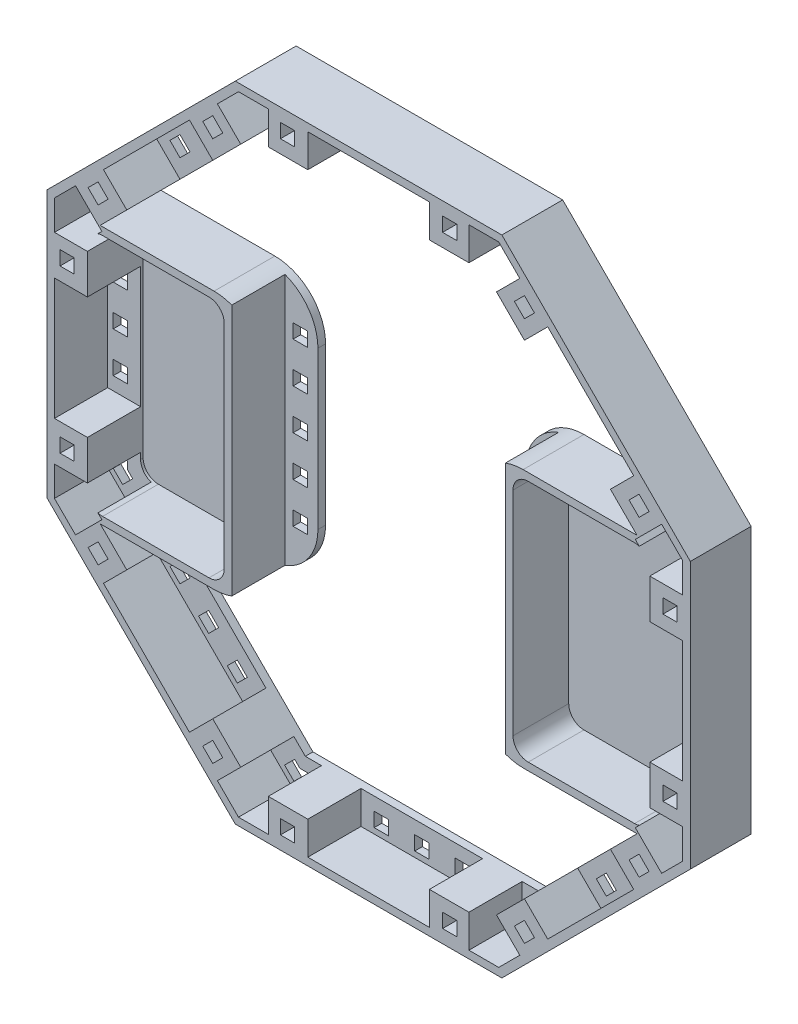
SolidWorks part; units mm, degrees
ref_plane "Plano frontal" through (0, 0, 0) normal (0, 0, 1) x (1, 0, 0)
ref_plane "Plano superior" through (0, 0, 0) normal (0, 1, 0) x (1, 0, 0)
ref_plane "Plano direito" through (0, 0, 0) normal (1, 0, 0) x (0, 0, -1)
sketch "Esboço1" plane through (0, 0, 0) normal (0, 0, 1) x (1, 0, 0)
  line L1 (63.5, -26.3026) -> (63.5, 26.3026)
  line L2 (63.5, 26.3026) -> (26.3026, 63.5)
  line L3 (26.3026, 63.5) -> (-26.3026, 63.5)
  line L4 (-26.3026, 63.5) -> (-63.5, 26.3026)
  line L5 (-63.5, 26.3026) -> (-63.5, -26.3026)
  line L6 (-63.5, -26.3026) -> (-26.3026, -63.5)
  line L7 (-26.3026, -63.5) -> (26.3026, -63.5)
  line L8 (26.3026, -63.5) -> (63.5, -26.3026)
  circle A0 centre (0, 0) radius 63.5 construction
  dimension "D1" = 127
extrude "Ressalto-extrusão1" add sketch "Esboço1" along normal blind 2.5
sketch "Esboço3"
sketch "Esboço2" plane through (0, 0, 0) normal (0, 0, -1) x (-1, 0, 0)
  line L0 (-42, 0) -> (42, 0) construction
  line L1 (-24, 0) -> (24, 0) construction
  line L3 (0, 0) -> (0, 75.734) construction
  line L4 (52.5, 24) -> (31.5, 24)
  line L5 (55.5, 21) -> (55.5, -21)
  line L6 (52.5, -24) -> (31.5, -24)
  line L7 (28.5, 21) -> (28.5, -21)
  line L8 (55.5, 24) -> (28.5, -24) construction
  line L9 (55.5, -24) -> (28.5, 24) construction
  line L10 (-55.5, -24) -> (-28.5, 24) construction
  line L11 (-55.5, 24) -> (-28.5, -24) construction
  line L13 (-28.5, 21) -> (-28.5, -21)
  line L14 (-52.5, -24) -> (-31.5, -24)
  line L15 (-55.5, 21) -> (-55.5, -21)
  line L16 (-52.5, 24) -> (-31.5, 24)
  line L17 (0, 0) -> (0, -57) construction
  line L19 (0, 63.5) -> (0, 43.5) construction
  line L20 (-26.3026, 63.5) -> (26.3026, 63.5) construction
  line L29 (63.5, 0) -> (-63.5, 0) construction
  line L30 (63.5, 26.3026) -> (63.5, -26.3026) construction
  line L31 (-63.5, -26.3026) -> (-63.5, 26.3026) construction
  arc A2 (31.5, 24) -> (28.5, 21) centre (31.5, 21) ccw
  arc A3 (31.5, -24) -> (28.5, -21) centre (31.5, -21) cw
  arc A4 (55.5, -21) -> (52.5, -24) centre (52.5, -21) cw
  arc A5 (52.5, 24) -> (55.5, 21) centre (52.5, 21) cw
  arc A6 (-52.5, 24) -> (-55.5, 21) centre (-52.5, 21) ccw
  arc A7 (-55.5, -21) -> (-52.5, -24) centre (-52.5, -21) ccw
  arc A8 (-31.5, -24) -> (-28.5, -21) centre (-31.5, -21) ccw
  arc A9 (-31.5, 24) -> (-28.5, 21) centre (-31.5, 21) cw
  dimension "D6" = 3
  dimension "D1" = 42
  dimension "D2" = 48
  dimension "D3" = 27
  dimension "D4" = 24
  dimension "D7" = 57
extrude "Corte-extrusão1" cut sketch "Esboço2" against normal through all
sketch "Esboço4" plane through (0, 0, 2.5) normal (0, 0, 1) x (1, 0, 0)
  line L0 (0, 0) -> (36.0624, 36.0624) construction
  line L1 (0, 0) -> (36.0624, -36.0624) construction
  line L2 (0, 0) -> (-36.0624, -36.0624) construction
  line L3 (0, 0) -> (-36.0624, 36.0624) construction
  line L4 (-38.0423, 36.0624) -> (-34.0825, 36.0624) construction
  line L11 (-36.0624, 34.0825) -> (-36.0624, 38.0423) construction
  line L12 (-36.0624, 34.0825) -> (-34.0825, 36.0624)
  line L13 (-38.0423, 36.0624) -> (-36.0624, 34.0825)
  line L14 (-36.0624, 38.0423) -> (-34.0825, 36.0624)
  line L15 (-38.0423, 36.0624) -> (-36.0624, 38.0423)
  line L16 (34.0825, 36.0624) -> (38.0423, 36.0624) construction
  line L17 (36.0624, 34.0825) -> (36.0624, 38.0423) construction
  line L18 (36.0624, 34.0825) -> (38.0423, 36.0624)
  line L19 (34.0825, 36.0624) -> (36.0624, 34.0825)
  line L20 (36.0624, 38.0423) -> (38.0423, 36.0624)
  line L21 (34.0825, 36.0624) -> (36.0624, 38.0423)
  line L22 (34.0825, -36.0624) -> (38.0423, -36.0624) construction
  line L23 (36.0624, -38.0423) -> (36.0624, -34.0825) construction
  line L24 (36.0624, -38.0423) -> (38.0423, -36.0624)
  line L25 (34.0825, -36.0624) -> (36.0624, -38.0423)
  line L26 (36.0624, -34.0825) -> (38.0423, -36.0624)
  line L27 (34.0825, -36.0624) -> (36.0624, -34.0825)
  line L28 (-38.0423, -36.0624) -> (-34.0825, -36.0624) construction
  line L29 (-36.0624, -38.0423) -> (-36.0624, -34.0825) construction
  line L30 (-36.0624, -38.0423) -> (-34.0825, -36.0624)
  line L31 (-38.0423, -36.0624) -> (-36.0624, -38.0423)
  line L32 (-36.0624, -34.0825) -> (-34.0825, -36.0624)
  line L33 (-38.0423, -36.0624) -> (-36.0624, -34.0825)
  circle A0 centre (0, 0) radius 51 construction
  circle A1 centre (-36.0624, 36.0624) radius 1.65 construction
  circle A2 centre (36.0624, 36.0624) radius 1.65 construction
  circle A3 centre (36.0624, -36.0624) radius 1.65 construction
  circle A4 centre (-36.0624, -36.0624) radius 1.65 construction
  point P10 (0, 0)
  point P17 (0, 0)
  point P21 (-36.0624, 36.0624)
  point P26 (36.0624, 36.0624)
  point P31 (36.0624, -36.0624)
  point P36 (-36.0624, -36.0624)
  dimension "D1" = 4
  dimension "D2" = 4
  dimension "D4" = 2.8
  dimension "D5" = 2.8
  dimension "D6" = 2.8
  dimension "D7" = 2.8
extrude "Corte-extrusão2" cut sketch "Esboço4" against normal blind 10.5
sketch "Esboço7" plane through (0, 0, 2.5) normal (0, 0, 1) x (1, 0, 0)
  line L0 (22.9889, -55.5) -> (55.5, -22.9889)
  line L1 (55.5, -22.9889) -> (55.5, 22.9889)
  line L2 (55.5, 22.9889) -> (22.9889, 55.5)
  line L3 (22.9889, 55.5) -> (-22.9889, 55.5)
  line L4 (-22.9889, 55.5) -> (-55.5, 22.9889)
  line L5 (-55.5, 22.9889) -> (-55.5, -22.9889)
  line L6 (-55.5, -22.9889) -> (-22.9889, -55.5)
  line L7 (-22.9889, -55.5) -> (22.9889, -55.5)
  line L8 (26.3026, -63.5) -> (63.5, -26.3026)
  line L9 (63.5, -26.3026) -> (63.5, 26.3026)
  line L10 (63.5, 26.3026) -> (26.3026, 63.5)
  line L11 (26.3026, 63.5) -> (-26.3026, 63.5)
  line L12 (-26.3026, 63.5) -> (-63.5, 26.3026)
  line L13 (-63.5, 26.3026) -> (-63.5, -26.3026)
  line L14 (-63.5, -26.3026) -> (-26.3026, -63.5)
  line L15 (-26.3026, -63.5) -> (26.3026, -63.5)
  line L16 (26.3026, -63.5) -> (63.5, -26.3026)
  line L17 (63.5, -26.3026) -> (63.5, 26.3026)
  line L18 (63.5, 26.3026) -> (26.3026, 63.5)
  line L19 (26.3026, 63.5) -> (-26.3026, 63.5)
  line L20 (-26.3026, 63.5) -> (-63.5, 26.3026)
  line L21 (-63.5, 26.3026) -> (-63.5, -26.3026)
  line L22 (-63.5, -26.3026) -> (-26.3026, -63.5)
  line L23 (-26.3026, -63.5) -> (26.3026, -63.5)
  dimension "D1" = 0
  dimension "D2" = 8
extrude "Ressalto-extrusão2" add sketch "Esboço7" along normal blind 9.5
sketch "Esboço5" plane through (0, 0, 0) normal (0, 0, -1) x (-1, 0, 0)
  line L0 (-44.9013, -44.9013) -> (-42.0729, -42.0729) construction
  line L1 (-26.3026, -63.5) -> (-63.5, -26.3026) construction
  line L2 (-47.7297, -34.4361) -> (-49.7096, -36.416)
  line L3 (-42.0729, -40.093) -> (-44.0528, -42.0729)
  line L4 (-42.0729, -40.093) -> (-40.093, -42.0729)
  line L5 (-40.093, -42.0729) -> (-42.0729, -44.0528)
  line L6 (-44.0528, -42.0729) -> (-42.0729, -44.0528)
  line L7 (-42.0729, -40.093) -> (-42.0729, -44.0528) construction
  line L8 (-40.093, -42.0729) -> (-44.0528, -42.0729) construction
  line L9 (-47.7297, -34.4361) -> (-45.7498, -36.416)
  line L10 (-45.7498, -36.416) -> (-47.7297, -38.3959)
  line L11 (-49.7096, -36.416) -> (-47.7297, -38.3959)
  line L12 (-47.7297, -34.4361) -> (-47.7297, -38.3959) construction
  line L13 (-45.7498, -36.416) -> (-49.7096, -36.416) construction
  line L14 (-53.3866, -28.7792) -> (-55.3665, -30.7591)
  line L15 (-53.3866, -28.7792) -> (-51.4067, -30.7591)
  line L16 (-51.4067, -30.7591) -> (-53.3866, -32.739)
  line L17 (-55.3665, -30.7591) -> (-53.3866, -32.739)
  line L18 (-53.3866, -28.7792) -> (-53.3866, -32.739) construction
  line L19 (-51.4067, -30.7591) -> (-55.3665, -30.7591) construction
  line L20 (-63.5, -26.3026) -> (-63.5, 26.3026) construction
  line L21 (63.5, 26.3026) -> (63.5, -26.3026) construction
  line L22 (-16, 24) -> (0, 24) construction
  line L23 (0, 24) -> (16, 24) construction
  line L24 (-9.4, 22.6) -> (-6.6, 25.4) construction
  line L25 (-9.4, 25.4) -> (-9.4, 22.6)
  line L26 (-9.4, 22.6) -> (-6.6, 22.6)
  line L27 (-9.4, 25.4) -> (-6.6, 22.6) construction
  line L28 (-30.7591, -51.4067) -> (-30.7591, -55.3665) construction
  line L29 (-28.7792, -53.3866) -> (-32.739, -53.3866) construction
  line L30 (-36.416, -45.7498) -> (-36.416, -49.7096) construction
  line L31 (-34.4361, -47.7297) -> (-38.3959, -47.7297) construction
  line L32 (-42.0729, -40.093) -> (-42.0729, -44.0528) construction
  line L33 (-40.093, -42.0729) -> (-44.0528, -42.0729) construction
  line L34 (-25.2256, -60.9) -> (-27.0822, -59.0434)
  line L35 (-25.1023, -57.0635) -> (-27.0822, -59.0434)
  line L36 (-9.4, 25.4) -> (-6.6, 25.4)
  line L37 (-6.6, 25.4) -> (-6.6, 22.6)
  line L38 (-30.7591, -55.3665) -> (-32.739, -53.3866)
  line L39 (-30.7591, -51.4067) -> (-32.739, -53.3866)
  line L40 (-28.7792, -53.3866) -> (-30.7591, -51.4067)
  line L41 (-28.7792, -53.3866) -> (-30.7591, -55.3665)
  line L42 (-36.416, -49.7096) -> (-38.3959, -47.7297)
  line L43 (-36.416, -45.7498) -> (-38.3959, -47.7297)
  line L44 (-34.4361, -47.7297) -> (-36.416, -45.7498)
  line L45 (-58.1, 6.6) -> (-60.9, 9.4) construction
  line L46 (-60.9, 6.6) -> (-58.1, 9.4) construction
  line L47 (-34.4361, -47.7297) -> (-36.416, -49.7096)
  line L48 (0, -63.5) -> (0, -59.5) construction
  line L49 (26.3026, -63.5) -> (-26.3026, -63.5) construction
  line L50 (-9.4, 6.6) -> (-6.6, 6.6)
  line L51 (1.4, -58.1) -> (-1.4, -58.1)
  line L52 (1.4, -58.1) -> (1.4, -60.9)
  line L53 (1.4, -60.9) -> (-1.4, -60.9)
  line L54 (-1.4, -58.1) -> (-1.4, -60.9)
  line L55 (1.4, -58.1) -> (-1.4, -60.9) construction
  line L56 (1.4, -60.9) -> (-1.4, -58.1) construction
  line L57 (-6.6, 9.4) -> (-6.6, 6.6)
  line L58 (-9.4, 9.4) -> (-6.6, 9.4)
  line L59 (-9.4, 9.4) -> (-9.4, 6.6)
  line L60 (-9.4, 6.6) -> (-6.6, 9.4) construction
  line L61 (-9.4, 9.4) -> (-6.6, 6.6) construction
  line L62 (-14.6, -58.1) -> (-17.4, -58.1)
  line L63 (-14.6, -58.1) -> (-14.6, -60.9)
  line L64 (-14.6, -60.9) -> (-17.4, -60.9)
  line L65 (-17.4, -58.1) -> (-17.4, -60.9)
  line L66 (-14.6, -58.1) -> (-17.4, -60.9) construction
  line L67 (-14.6, -60.9) -> (-17.4, -58.1) construction
  line L68 (-22.6, -58.1) -> (-24.0658, -58.1)
  line L69 (-22.6, -58.1) -> (-22.6, -60.9)
  line L70 (-22.6, -60.9) -> (-25.2256, -60.9)
  line L71 (6.6, 22.6) -> (9.4, 25.4) construction
  line L72 (6.6, 25.4) -> (6.6, 22.6)
  line L73 (6.6, 22.6) -> (9.4, 22.6)
  line L74 (6.6, 25.4) -> (9.4, 22.6) construction
  line L75 (6.6, 25.4) -> (9.4, 25.4)
  line L76 (9.4, 25.4) -> (9.4, 22.6)
  line L77 (-9.4, -1.4) -> (-6.6, -1.4)
  line L78 (-25.4, -58.1) -> (-25.4, -59.0434) [skipped]
  line L80 (-24.0658, -58.1) -> (-25.1023, -57.0635)
  line L82 (-23.5434, -59.0434) -> (-24, -59.5) construction
  line L83 (-25.4, 46.6) -> (-22.6, 49.4) construction
  line L84 (-24, -59.5) -> (-24.4566, -59.0434) construction
  line L85 (6.6, -25.4) -> (9.4, -22.6) construction
  line L86 (6.6, -22.6) -> (9.4, -25.4) construction
  line L87 (9.4, -25.4) -> (9.4, -22.6)
  line L88 (6.6, -25.4) -> (9.4, -25.4)
  line L89 (6.6, -22.6) -> (9.4, -22.6)
  line L90 (6.6, -25.4) -> (6.6, -22.6)
  line L91 (-9.4, -25.4) -> (-6.6, -22.6) construction
  line L92 (-9.4, -22.6) -> (-6.6, -25.4) construction
  line L93 (-6.6, -25.4) -> (-6.6, -22.6)
  line L94 (-9.4, -25.4) -> (-6.6, -25.4)
  line L95 (-9.4, -22.6) -> (-6.6, -22.6)
  line L96 (-9.4, -25.4) -> (-9.4, -22.6)
  line L97 (-60.25, 0) -> (60.25, 0) construction
  line L98 (0, 0) -> (0, 63.5) construction
  line L99 (-26.3026, 63.5) -> (26.3026, 63.5) construction
  line L100 (-25.4, 49.4) -> (-22.6, 46.6) construction
  line L101 (-6.6, 1.4) -> (-6.6, -1.4)
  line L102 (-9.4, 1.4) -> (-6.6, 1.4)
  line L103 (-9.4, 1.4) -> (-9.4, -1.4)
  line L104 (-9.4, -1.4) -> (-6.6, 1.4) construction
  line L105 (-9.4, 1.4) -> (-6.6, -1.4) construction
  line L106 (14.6, -60.9) -> (17.4, -58.1) construction
  line L107 (14.6, -58.1) -> (17.4, -60.9) construction
  line L108 (-9.4, -9.4) -> (-6.6, -9.4)
  line L109 (-6.6, -6.6) -> (-6.6, -9.4)
  line L110 (40.093, -42.0729) -> (44.0528, -42.0729) construction
  line L111 (42.0729, -40.093) -> (42.0729, -44.0528) construction
  line L112 (34.4361, -47.7297) -> (38.3959, -47.7297) construction
  line L113 (36.416, -45.7498) -> (36.416, -49.7096) construction
  line L114 (28.7792, -53.3866) -> (32.739, -53.3866) construction
  line L115 (30.7591, -51.4067) -> (30.7591, -55.3665) construction
  line L116 (-9.4, -6.6) -> (-6.6, -6.6)
  line L117 (-9.4, -6.6) -> (-9.4, -9.4)
  line L118 (-9.4, -9.4) -> (-6.6, -6.6) construction
  line L119 (51.4067, -30.7591) -> (55.3665, -30.7591) construction
  line L120 (53.3866, -28.7792) -> (53.3866, -32.739) construction
  line L121 (45.7498, -36.416) -> (49.7096, -36.416) construction
  line L122 (47.7297, -34.4361) -> (47.7297, -38.3959) construction
  line L123 (40.093, -42.0729) -> (44.0528, -42.0729) construction
  line L124 (42.0729, -40.093) -> (42.0729, -44.0528) construction
  line L125 (44.9013, -44.9013) -> (42.0729, -42.0729) construction
  line L126 (-9.4, -6.6) -> (-6.6, -9.4) construction
  line L127 (9.4, -6.6) -> (6.6, -9.4) construction
  line L128 (9.4, -9.4) -> (6.6, -6.6) construction
  line L129 (9.4, 1.4) -> (6.6, -1.4) construction
  line L130 (9.4, -1.4) -> (6.6, 1.4) construction
  line L131 (9.4, 9.4) -> (6.6, 6.6) construction
  line L132 (9.4, 6.6) -> (6.6, 9.4) construction
  line L133 (24.0658, -58.1) -> (25.1023, -57.0635)
  line L134 (60.9, -25.2256) -> (59.0434, -27.0822)
  line L135 (57.0635, -25.1023) -> (59.0434, -27.0822)
  line L136 (58.1, -6.6) -> (58.1, -9.4)
  line L137 (58.1, 1.4) -> (58.1, -1.4)
  line L138 (22.6, -60.9) -> (25.2256, -60.9)
  line L139 (22.6, -58.1) -> (22.6, -60.9)
  line L140 (22.6, -58.1) -> (24.0658, -58.1)
  line L141 (17.4, -58.1) -> (17.4, -60.9)
  line L142 (14.6, -60.9) -> (17.4, -60.9)
  line L143 (14.6, -58.1) -> (14.6, -60.9)
  line L144 (14.6, -58.1) -> (17.4, -58.1)
  line L145 (9.4, -6.6) -> (9.4, -9.4)
  line L146 (9.4, -6.6) -> (6.6, -6.6)
  line L147 (6.6, -6.6) -> (6.6, -9.4)
  line L148 (9.4, -9.4) -> (6.6, -9.4)
  line L149 (34.4361, -47.7297) -> (36.416, -49.7096)
  line L150 (40.093, -42.0729) -> (42.0729, -44.0528)
  line L151 (42.0729, -40.093) -> (44.0528, -42.0729)
  line L152 (34.4361, -47.7297) -> (36.416, -45.7498)
  line L153 (36.416, -45.7498) -> (38.3959, -47.7297)
  line L154 (36.416, -49.7096) -> (38.3959, -47.7297)
  line L155 (28.7792, -53.3866) -> (30.7591, -55.3665)
  line L156 (28.7792, -53.3866) -> (30.7591, -51.4067)
  line L157 (30.7591, -51.4067) -> (32.739, -53.3866)
  line L158 (30.7591, -55.3665) -> (32.739, -53.3866)
  line L159 (58.1, 1.4) -> (60.9, 1.4)
  line L160 (25.1023, -57.0635) -> (27.0822, -59.0434)
  line L161 (25.2256, -60.9) -> (27.0822, -59.0434)
  line L162 (60.9, 1.4) -> (60.9, -1.4)
  line L163 (58.1, -1.4) -> (60.9, -1.4)
  line L164 (58.1, -6.6) -> (60.9, -6.6)
  line L165 (60.9, -6.6) -> (60.9, -9.4)
  line L166 (55.3665, -30.7591) -> (53.3866, -32.739)
  line L167 (51.4067, -30.7591) -> (53.3866, -32.739)
  line L168 (53.3866, -28.7792) -> (51.4067, -30.7591)
  line L169 (53.3866, -28.7792) -> (55.3665, -30.7591)
  line L170 (49.7096, -36.416) -> (47.7297, -38.3959)
  line L171 (45.7498, -36.416) -> (47.7297, -38.3959)
  line L172 (47.7297, -34.4361) -> (45.7498, -36.416)
  line L173 (44.0528, -42.0729) -> (42.0729, -44.0528)
  line L174 (-58.1, 14.6) -> (-60.9, 17.4) construction
  line L175 (42.0729, -40.093) -> (40.093, -42.0729)
  line L176 (-60.9, 14.6) -> (-58.1, 17.4) construction
  line L177 (47.7297, -34.4361) -> (49.7096, -36.416)
  line L178 (44.9013, 44.9013) -> (42.0729, 42.0729) construction
  line L179 (42.0729, 40.093) -> (42.0729, 44.0528) construction
  line L180 (40.093, 42.0729) -> (44.0528, 42.0729) construction
  line L181 (47.7297, 34.4361) -> (47.7297, 38.3959) construction
  line L182 (45.7498, 36.416) -> (49.7096, 36.416) construction
  line L183 (53.3866, 28.7792) -> (53.3866, 32.739) construction
  line L184 (51.4067, 30.7591) -> (55.3665, 30.7591) construction
  line L185 (58.1, -9.4) -> (60.9, -9.4)
  line L186 (58.1, -14.6) -> (58.1, -17.4)
  line L187 (30.7591, 51.4067) -> (30.7591, 55.3665) construction
  line L188 (28.7792, 53.3866) -> (32.739, 53.3866) construction
  line L189 (36.416, 45.7498) -> (36.416, 49.7096) construction
  line L190 (34.4361, 47.7297) -> (38.3959, 47.7297) construction
  line L191 (42.0729, 40.093) -> (42.0729, 44.0528) construction
  line L192 (40.093, 42.0729) -> (44.0528, 42.0729) construction
  line L193 (9.4, 1.4) -> (9.4, -1.4)
  line L194 (9.4, 1.4) -> (6.6, 1.4)
  line L195 (14.6, 58.1) -> (17.4, 60.9) construction
  line L196 (14.6, 60.9) -> (17.4, 58.1) construction
  line L197 (58.1, -14.6) -> (60.9, -14.6)
  line L198 (60.9, -14.6) -> (60.9, -17.4)
  line L199 (58.1, -17.4) -> (60.9, -17.4)
  line L200 (58.1, -22.6) -> (58.1, -24.0658)
  line L201 (58.1, -22.6) -> (60.9, -22.6)
  line L202 (60.9, -22.6) -> (60.9, -25.2256)
  line L203 (58.1, -24.0658) -> (57.0635, -25.1023)
  line L204 (58.1, 24.0658) -> (57.0635, 25.1023)
  line L205 (-14.6, 60.9) -> (-17.4, 58.1) construction
  line L206 (-14.6, 58.1) -> (-17.4, 60.9) construction
  line L207 (6.6, 1.4) -> (6.6, -1.4)
  line L208 (9.4, -1.4) -> (6.6, -1.4)
  line L209 (1.4, 60.9) -> (-1.4, 58.1) construction
  line L210 (1.4, 58.1) -> (-1.4, 60.9) construction
  line L211 (0, 63.5) -> (0, 59.5) construction
  line L212 (-40.093, 42.0729) -> (-44.0528, 42.0729) construction
  line L213 (-42.0729, 40.093) -> (-42.0729, 44.0528) construction
  line L214 (-34.4361, 47.7297) -> (-38.3959, 47.7297) construction
  line L215 (-36.416, 45.7498) -> (-36.416, 49.7096) construction
  line L216 (-28.7792, 53.3866) -> (-32.739, 53.3866) construction
  line L217 (-30.7591, 51.4067) -> (-30.7591, 55.3665) construction
  line L218 (60.9, 22.6) -> (60.9, 25.2256)
  line L219 (58.1, 22.6) -> (60.9, 22.6)
  line L220 (-51.4067, 30.7591) -> (-55.3665, 30.7591) construction
  line L221 (-53.3866, 28.7792) -> (-53.3866, 32.739) construction
  line L222 (-45.7498, 36.416) -> (-49.7096, 36.416) construction
  line L223 (-47.7297, 34.4361) -> (-47.7297, 38.3959) construction
  line L224 (-40.093, 42.0729) -> (-44.0528, 42.0729) construction
  line L225 (-42.0729, 40.093) -> (-42.0729, 44.0528) construction
  line L226 (-44.9013, 44.9013) -> (-42.0729, 42.0729) construction
  line L227 (47.7297, 34.4361) -> (49.7096, 36.416)
  line L228 (42.0729, 40.093) -> (44.0528, 42.0729)
  line L229 (42.0729, 40.093) -> (40.093, 42.0729)
  line L230 (40.093, 42.0729) -> (42.0729, 44.0528)
  line L231 (44.0528, 42.0729) -> (42.0729, 44.0528)
  line L232 (47.7297, 34.4361) -> (45.7498, 36.416)
  line L233 (45.7498, 36.416) -> (47.7297, 38.3959)
  line L234 (49.7096, 36.416) -> (47.7297, 38.3959)
  line L235 (53.3866, 28.7792) -> (55.3665, 30.7591)
  line L236 (53.3866, 28.7792) -> (51.4067, 30.7591)
  line L237 (51.4067, 30.7591) -> (53.3866, 32.739)
  line L238 (55.3665, 30.7591) -> (53.3866, 32.739)
  line L239 (58.1, 22.6) -> (58.1, 24.0658)
  line L240 (58.1, 17.4) -> (60.9, 17.4)
  line L241 (60.9, 14.6) -> (60.9, 17.4)
  line L242 (58.1, 14.6) -> (60.9, 14.6)
  line L243 (25.2256, 60.9) -> (27.0822, 59.0434)
  line L244 (25.1023, 57.0635) -> (27.0822, 59.0434)
  line L245 (58.1, 14.6) -> (58.1, 17.4)
  line L246 (30.7591, 55.3665) -> (32.739, 53.3866)
  line L247 (30.7591, 51.4067) -> (32.739, 53.3866)
  line L248 (28.7792, 53.3866) -> (30.7591, 51.4067)
  line L249 (28.7792, 53.3866) -> (30.7591, 55.3665)
  line L250 (36.416, 49.7096) -> (38.3959, 47.7297)
  line L251 (36.416, 45.7498) -> (38.3959, 47.7297)
  line L252 (34.4361, 47.7297) -> (36.416, 45.7498)
  line L253 (-60.9, -14.6) -> (-58.1, -17.4) construction
  line L254 (-58.1, -14.6) -> (-60.9, -17.4) construction
  line L255 (34.4361, 47.7297) -> (36.416, 49.7096)
  line L256 (9.4, 9.4) -> (9.4, 6.6)
  line L257 (9.4, 9.4) -> (6.6, 9.4)
  line L258 (6.6, 9.4) -> (6.6, 6.6)
  line L259 (9.4, 6.6) -> (6.6, 6.6)
  line L260 (14.6, 58.1) -> (17.4, 58.1)
  line L261 (14.6, 58.1) -> (14.6, 60.9)
  line L262 (14.6, 60.9) -> (17.4, 60.9)
  line L263 (17.4, 58.1) -> (17.4, 60.9)
  line L264 (22.6, 58.1) -> (24.0658, 58.1)
  line L265 (22.6, 58.1) -> (22.6, 60.9)
  line L266 (22.6, 60.9) -> (25.2256, 60.9)
  line L267 (24.0658, 58.1) -> (25.1023, 57.0635)
  line L268 (58.1, 9.4) -> (60.9, 9.4)
  line L269 (60.9, 6.6) -> (60.9, 9.4)
  line L270 (58.1, 6.6) -> (60.9, 6.6)
  line L271 (58.1, 6.6) -> (58.1, 9.4)
  line L272 (57.0635, 25.1023) -> (59.0434, 27.0822)
  line L273 (60.9, 25.2256) -> (59.0434, 27.0822)
  line L274 (63.5, 0) -> (59.5, 0) construction
  line L275 (58.1, 1.4) -> (60.9, -1.4) construction
  line L276 (60.9, 1.4) -> (58.1, -1.4) construction
  line L277 (58.1, -6.6) -> (60.9, -9.4) construction
  line L278 (60.9, -6.6) -> (58.1, -9.4) construction
  line L279 (58.1, -14.6) -> (60.9, -17.4) construction
  line L280 (60.9, -14.6) -> (58.1, -17.4) construction
  line L281 (60.9, 14.6) -> (58.1, 17.4) construction
  line L282 (-24.0658, 58.1) -> (-25.1023, 57.0635)
  line L283 (-22.6, 60.9) -> (-25.2256, 60.9)
  line L284 (-22.6, 58.1) -> (-22.6, 60.9)
  line L285 (-22.6, 58.1) -> (-24.0658, 58.1)
  line L286 (-17.4, 58.1) -> (-17.4, 60.9)
  line L287 (-14.6, 60.9) -> (-17.4, 60.9)
  line L288 (-14.6, 58.1) -> (-14.6, 60.9)
  line L289 (-14.6, 58.1) -> (-17.4, 58.1)
  line L290 (-16, 59.5) -> (0, 59.5) construction
  line L291 (-9.4, 58.1) -> (-9.4, 60.9)
  line L292 (-6.6, 60.9) -> (-9.4, 58.1) construction
  line L293 (-1.4, 58.1) -> (-1.4, 60.9)
  line L294 (1.4, 60.9) -> (-1.4, 60.9)
  line L295 (1.4, 58.1) -> (1.4, 60.9)
  line L296 (1.4, 58.1) -> (-1.4, 58.1)
  line L297 (-6.6, 58.1) -> (-6.6, 60.9)
  line L298 (-34.4361, 47.7297) -> (-36.416, 49.7096)
  line L299 (-40.093, 42.0729) -> (-42.0729, 44.0528)
  line L300 (-42.0729, 40.093) -> (-44.0528, 42.0729)
  line L301 (-34.4361, 47.7297) -> (-36.416, 45.7498)
  line L302 (-36.416, 45.7498) -> (-38.3959, 47.7297)
  line L303 (-36.416, 49.7096) -> (-38.3959, 47.7297)
  line L304 (-28.7792, 53.3866) -> (-30.7591, 55.3665)
  line L305 (-28.7792, 53.3866) -> (-30.7591, 51.4067)
  line L306 (-30.7591, 51.4067) -> (-32.739, 53.3866)
  line L307 (-30.7591, 55.3665) -> (-32.739, 53.3866)
  line L308 (58.1, 14.6) -> (60.9, 17.4) construction
  line L309 (-25.1023, 57.0635) -> (-27.0822, 59.0434)
  line L310 (-25.2256, 60.9) -> (-27.0822, 59.0434)
  line L311 (60.9, 6.6) -> (58.1, 9.4) construction
  line L312 (58.1, 6.6) -> (60.9, 9.4) construction
  line L313 (-6.6, 60.9) -> (-9.4, 60.9)
  line L314 (-6.6, 58.1) -> (-9.4, 58.1)
  line L315 (-55.3665, 30.7591) -> (-53.3866, 32.739)
  line L316 (-51.4067, 30.7591) -> (-53.3866, 32.739)
  line L317 (-53.3866, 28.7792) -> (-51.4067, 30.7591)
  line L318 (-53.3866, 28.7792) -> (-55.3665, 30.7591)
  line L319 (-49.7096, 36.416) -> (-47.7297, 38.3959)
  line L320 (-45.7498, 36.416) -> (-47.7297, 38.3959)
  line L321 (-47.7297, 34.4361) -> (-45.7498, 36.416)
  line L322 (-44.0528, 42.0729) -> (-42.0729, 44.0528)
  line L323 (-60.9, -6.6) -> (-58.1, -9.4) construction
  line L324 (-42.0729, 40.093) -> (-40.093, 42.0729)
  line L325 (-58.1, -6.6) -> (-60.9, -9.4) construction
  line L326 (-47.7297, 34.4361) -> (-49.7096, 36.416)
  line L327 (-17.4, 46.6) -> (-14.6, 49.4) construction
  line L328 (1.4, 1.4) -> (-1.4, 1.4)
  line L329 (1.4, 1.4) -> (1.4, -1.4)
  line L330 (1.4, -1.4) -> (-1.4, -1.4)
  line L331 (-1.4, 1.4) -> (-1.4, -1.4)
  line L332 (1.4, 1.4) -> (-1.4, -1.4) construction
  line L333 (1.4, -1.4) -> (-1.4, 1.4) construction
  line L334 (-6.6, 58.1) -> (-9.4, 60.9) construction
  line L335 (6.6, 58.1) -> (9.4, 60.9) construction
  line L336 (6.6, 60.9) -> (9.4, 58.1) construction
  line L337 (6.6, 58.1) -> (9.4, 58.1)
  line L338 (6.6, 60.9) -> (9.4, 60.9)
  line L339 (6.6, 58.1) -> (6.6, 60.9)
  line L340 (9.4, 58.1) -> (9.4, 60.9)
  line L341 (6.6, -60.9) -> (9.4, -58.1) construction
  line L342 (6.6, -58.1) -> (9.4, -60.9) construction
  line L343 (9.4, -58.1) -> (9.4, -60.9)
  line L344 (6.6, -58.1) -> (6.6, -60.9)
  line L345 (25.4, 1.4) -> (22.6, -1.4) construction
  line L346 (25.4, -1.4) -> (22.6, 1.4) construction
  line L347 (25.4, 1.4) -> (25.4, -1.4)
  line L348 (25.4, 1.4) -> (22.6, 1.4)
  line L349 (22.6, 1.4) -> (22.6, -1.4)
  line L350 (25.4, -1.4) -> (22.6, -1.4)
  line L351 (33.4, 1.4) -> (30.6, -1.4) construction
  line L352 (33.4, -1.4) -> (30.6, 1.4) construction
  line L353 (33.4, 1.4) -> (33.4, -1.4) [skipped]
  line L354 (33.4, 1.4) -> (30.6, 1.4) [skipped]
  line L355 (30.6, 1.4) -> (30.6, -1.4) [skipped]
  line L356 (33.4, -1.4) -> (30.6, -1.4) [skipped]
  line L357 (41.4, 1.4) -> (38.6, -1.4) construction
  line L358 (41.4, -1.4) -> (38.6, 1.4) construction
  line L359 (41.4, 1.4) -> (41.4, -1.4) [skipped]
  line L360 (41.4, 1.4) -> (38.6, 1.4) [skipped]
  line L361 (38.6, 1.4) -> (38.6, -1.4) [skipped]
  line L362 (41.4, -1.4) -> (38.6, -1.4) [skipped]
  line L363 (49.4, 1.4) -> (46.6, -1.4) construction
  line L364 (49.4, -1.4) -> (46.6, 1.4) construction
  line L365 (49.4, 1.4) -> (49.4, -1.4) [skipped]
  line L366 (49.4, 1.4) -> (46.6, 1.4) [skipped]
  line L367 (46.6, 1.4) -> (46.6, -1.4) [skipped]
  line L368 (49.4, -1.4) -> (46.6, -1.4) [skipped]
  line L369 (6.6, -60.9) -> (9.4, -60.9)
  line L370 (6.6, -58.1) -> (9.4, -58.1)
  line L371 (-6.6, -58.1) -> (-9.4, -60.9) construction
  line L372 (-6.6, -60.9) -> (-9.4, -58.1) construction
  line L373 (-6.6, -58.1) -> (-9.4, -58.1)
  line L374 (-6.6, -60.9) -> (-9.4, -60.9)
  line L375 (-6.6, -58.1) -> (-6.6, -60.9)
  line L376 (-9.4, -58.1) -> (-9.4, -60.9)
  line L387 (33.4, 9.4) -> (30.6, 6.6) construction
  line L388 (33.4, 6.6) -> (30.6, 9.4) construction
  line L389 (33.4, 9.4) -> (33.4, 6.6) [skipped]
  line L390 (33.4, 9.4) -> (30.6, 9.4) [skipped]
  line L391 (30.6, 9.4) -> (30.6, 6.6) [skipped]
  line L392 (33.4, 6.6) -> (30.6, 6.6) [skipped]
  line L393 (41.4, 9.4) -> (38.6, 6.6) construction
  line L394 (41.4, 6.6) -> (38.6, 9.4) construction
  line L395 (41.4, 9.4) -> (41.4, 6.6) [skipped]
  line L396 (41.4, 9.4) -> (38.6, 9.4) [skipped]
  line L397 (38.6, 9.4) -> (38.6, 6.6) [skipped]
  line L398 (41.4, 6.6) -> (38.6, 6.6) [skipped]
  line L399 (49.4, 9.4) -> (46.6, 6.6) construction
  line L400 (49.4, 6.6) -> (46.6, 9.4) construction
  line L401 (49.4, 9.4) -> (49.4, 6.6) [skipped]
  line L402 (49.4, 9.4) -> (46.6, 9.4) [skipped]
  line L403 (46.6, 9.4) -> (46.6, 6.6) [skipped]
  line L404 (49.4, 6.6) -> (46.6, 6.6) [skipped]
  line L405 (9.4, 17.4) -> (6.6, 14.6) construction
  line L406 (9.4, 14.6) -> (6.6, 17.4) construction
  line L407 (9.4, 17.4) -> (9.4, 14.6)
  line L408 (9.4, 17.4) -> (6.6, 17.4)
  line L409 (6.6, 17.4) -> (6.6, 14.6)
  line L410 (9.4, 14.6) -> (6.6, 14.6)
  line L411 (17.4, 17.4) -> (14.6, 14.6) construction
  line L412 (17.4, 14.6) -> (14.6, 17.4) construction
  line L413 (17.4, 17.4) -> (17.4, 14.6) construction
  line L414 (17.4, 17.4) -> (14.6, 17.4) construction
  line L415 (14.6, 17.4) -> (14.6, 14.6) construction
  line L416 (17.4, 14.6) -> (14.6, 14.6) construction
  line L417 (25.4, 17.4) -> (22.6, 14.6) construction
  line L418 (25.4, 14.6) -> (22.6, 17.4) construction
  line L419 (25.4, 17.4) -> (25.4, 14.6)
  line L420 (25.4, 17.4) -> (22.6, 17.4)
  line L421 (22.6, 17.4) -> (22.6, 14.6)
  line L422 (25.4, 14.6) -> (22.6, 14.6)
  line L423 (33.4, 17.4) -> (30.6, 14.6) construction
  line L424 (33.4, 14.6) -> (30.6, 17.4) construction
  line L425 (33.4, 17.4) -> (33.4, 14.6) [skipped]
  line L426 (33.4, 17.4) -> (30.6, 17.4) [skipped]
  line L427 (30.6, 17.4) -> (30.6, 14.6) [skipped]
  line L428 (33.4, 14.6) -> (30.6, 14.6) [skipped]
  line L429 (41.4, 17.4) -> (38.6, 14.6) construction
  line L430 (41.4, 14.6) -> (38.6, 17.4) construction
  line L431 (41.4, 17.4) -> (41.4, 14.6) [skipped]
  line L432 (41.4, 17.4) -> (38.6, 17.4) [skipped]
  line L433 (38.6, 17.4) -> (38.6, 14.6) [skipped]
  line L434 (41.4, 14.6) -> (38.6, 14.6) [skipped]
  line L435 (49.4, 17.4) -> (46.6, 14.6) construction
  line L436 (49.4, 14.6) -> (46.6, 17.4) construction
  line L437 (49.4, 17.4) -> (49.4, 14.6) [skipped]
  line L438 (49.4, 17.4) -> (46.6, 17.4) [skipped]
  line L439 (46.6, 17.4) -> (46.6, 14.6) [skipped]
  line L440 (49.4, 14.6) -> (46.6, 14.6) [skipped]
  line L441 (9.4, 25.4) -> (6.6, 22.6) construction
  line L442 (9.4, 22.6) -> (6.6, 25.4) construction
  line L443 (9.4, 25.4) -> (9.4, 22.6) [skipped]
  line L444 (9.4, 25.4) -> (6.6, 25.4) [skipped]
  line L445 (6.6, 25.4) -> (6.6, 22.6) [skipped]
  line L446 (9.4, 22.6) -> (6.6, 22.6) [skipped]
  line L447 (17.4, 25.4) -> (14.6, 22.6) construction
  line L448 (17.4, 22.6) -> (14.6, 25.4) construction
  line L449 (17.4, 25.4) -> (17.4, 22.6)
  line L450 (17.4, 25.4) -> (14.6, 25.4)
  line L451 (14.6, 25.4) -> (14.6, 22.6)
  line L452 (17.4, 22.6) -> (14.6, 22.6)
  line L459 (33.4, 25.4) -> (30.6, 22.6) construction
  line L460 (33.4, 22.6) -> (30.6, 25.4) construction
  line L461 (33.4, 25.4) -> (33.4, 22.6) [skipped]
  line L462 (33.4, 25.4) -> (30.6, 25.4) [skipped]
  line L463 (30.6, 25.4) -> (30.6, 22.6) [skipped]
  line L464 (33.4, 22.6) -> (30.6, 22.6) [skipped]
  line L465 (41.4, 25.4) -> (38.6, 22.6) construction
  line L466 (41.4, 22.6) -> (38.6, 25.4) construction
  line L467 (41.4, 25.4) -> (41.4, 22.6) [skipped]
  line L468 (41.4, 25.4) -> (38.6, 25.4) [skipped]
  line L469 (38.6, 25.4) -> (38.6, 22.6) [skipped]
  line L470 (41.4, 22.6) -> (38.6, 22.6) [skipped]
  line L471 (49.4, 25.4) -> (46.6, 22.6) construction
  line L472 (49.4, 22.6) -> (46.6, 25.4) construction
  line L473 (49.4, 25.4) -> (49.4, 22.6) [skipped]
  line L474 (49.4, 25.4) -> (46.6, 25.4) [skipped]
  line L475 (46.6, 25.4) -> (46.6, 22.6) [skipped]
  line L476 (49.4, 22.6) -> (46.6, 22.6) [skipped]
  line L477 (9.4, 33.4) -> (6.6, 30.6) construction
  line L478 (9.4, 30.6) -> (6.6, 33.4) construction
  line L479 (9.4, 33.4) -> (9.4, 30.6)
  line L480 (9.4, 33.4) -> (6.6, 33.4)
  line L481 (6.6, 33.4) -> (6.6, 30.6)
  line L482 (9.4, 30.6) -> (6.6, 30.6)
  line L483 (17.4, 33.4) -> (14.6, 30.6) construction
  line L484 (17.4, 30.6) -> (14.6, 33.4) construction
  line L485 (17.4, 33.4) -> (17.4, 30.6)
  line L486 (17.4, 33.4) -> (14.6, 33.4)
  line L487 (14.6, 33.4) -> (14.6, 30.6)
  line L488 (17.4, 30.6) -> (14.6, 30.6)
  line L489 (25.4, 33.4) -> (22.6, 30.6) construction
  line L490 (25.4, 30.6) -> (22.6, 33.4) construction
  line L491 (25.4, 33.4) -> (25.4, 30.6)
  line L492 (25.4, 33.4) -> (22.6, 33.4)
  line L493 (22.6, 33.4) -> (22.6, 30.6)
  line L494 (25.4, 30.6) -> (22.6, 30.6)
  line L495 (33.4, 33.4) -> (30.6, 30.6) construction
  line L496 (33.4, 30.6) -> (30.6, 33.4) construction
  line L497 (33.4, 33.4) -> (33.4, 30.6)
  line L498 (33.4, 33.4) -> (30.6, 33.4)
  line L499 (30.6, 33.4) -> (30.6, 30.6)
  line L500 (33.4, 30.6) -> (30.6, 30.6)
  line L501 (41.4, 33.4) -> (38.6, 30.6) construction
  line L502 (41.4, 30.6) -> (38.6, 33.4) construction
  line L503 (41.4, 33.4) -> (41.4, 30.6)
  line L504 (41.4, 33.4) -> (38.6, 33.4)
  line L505 (38.6, 33.4) -> (38.6, 30.6)
  line L506 (41.4, 30.6) -> (38.6, 30.6)
  line L513 (9.4, 41.4) -> (6.6, 38.6) construction
  line L514 (9.4, 38.6) -> (6.6, 41.4) construction
  line L515 (9.4, 41.4) -> (9.4, 38.6)
  line L516 (9.4, 41.4) -> (6.6, 41.4)
  line L517 (6.6, 41.4) -> (6.6, 38.6)
  line L518 (9.4, 38.6) -> (6.6, 38.6)
  line L519 (17.4, 41.4) -> (14.6, 38.6) construction
  line L520 (17.4, 38.6) -> (14.6, 41.4) construction
  line L521 (17.4, 41.4) -> (17.4, 38.6)
  line L522 (17.4, 41.4) -> (14.6, 41.4)
  line L523 (14.6, 41.4) -> (14.6, 38.6)
  line L524 (17.4, 38.6) -> (14.6, 38.6)
  line L525 (25.4, 41.4) -> (22.6, 38.6) construction
  line L526 (25.4, 38.6) -> (22.6, 41.4) construction
  line L527 (25.4, 41.4) -> (25.4, 38.6)
  line L528 (25.4, 41.4) -> (22.6, 41.4)
  line L529 (22.6, 41.4) -> (22.6, 38.6)
  line L530 (25.4, 38.6) -> (22.6, 38.6)
  line L531 (33.4, 41.4) -> (30.6, 38.6) construction
  line L532 (33.4, 38.6) -> (30.6, 41.4) construction
  line L533 (33.4, 41.4) -> (33.4, 38.6)
  line L534 (33.4, 41.4) -> (30.6, 41.4)
  line L535 (30.6, 41.4) -> (30.6, 38.6)
  line L536 (33.4, 38.6) -> (30.6, 38.6)
  line L537 (41.4, 41.4) -> (38.6, 38.6) construction
  line L538 (41.4, 38.6) -> (38.6, 41.4) construction
  line L539 (41.4, 41.4) -> (41.4, 38.6) [skipped]
  line L540 (41.4, 41.4) -> (38.6, 41.4) [skipped]
  line L541 (38.6, 41.4) -> (38.6, 38.6) [skipped]
  line L542 (41.4, 38.6) -> (38.6, 38.6) [skipped]
  line L543 (49.4, 41.4) -> (46.6, 38.6) construction
  line L544 (49.4, 38.6) -> (46.6, 41.4) construction
  line L545 (49.4, 41.4) -> (49.4, 38.6) [skipped]
  line L546 (49.4, 41.4) -> (46.6, 41.4) [skipped]
  line L547 (46.6, 41.4) -> (46.6, 38.6) [skipped]
  line L548 (49.4, 38.6) -> (46.6, 38.6) [skipped]
  line L549 (9.4, 49.4) -> (6.6, 46.6) construction
  line L550 (9.4, 46.6) -> (6.6, 49.4) construction
  line L551 (9.4, 49.4) -> (9.4, 46.6)
  line L552 (9.4, 49.4) -> (6.6, 49.4)
  line L553 (6.6, 49.4) -> (6.6, 46.6)
  line L554 (9.4, 46.6) -> (6.6, 46.6)
  line L555 (17.4, 49.4) -> (14.6, 46.6) construction
  line L556 (17.4, 46.6) -> (14.6, 49.4) construction
  line L557 (17.4, 49.4) -> (17.4, 46.6)
  line L558 (17.4, 49.4) -> (14.6, 49.4)
  line L559 (14.6, 49.4) -> (14.6, 46.6)
  line L560 (17.4, 46.6) -> (14.6, 46.6)
  line L561 (25.4, 49.4) -> (22.6, 46.6) construction
  line L562 (25.4, 46.6) -> (22.6, 49.4) construction
  line L563 (25.4, 49.4) -> (25.4, 46.6)
  line L564 (25.4, 49.4) -> (22.6, 49.4)
  line L565 (22.6, 49.4) -> (22.6, 46.6)
  line L566 (25.4, 46.6) -> (22.6, 46.6)
  line L573 (41.4, 49.4) -> (38.6, 46.6) construction
  line L574 (41.4, 46.6) -> (38.6, 49.4) construction
  line L575 (41.4, 49.4) -> (41.4, 46.6) [skipped]
  line L576 (41.4, 49.4) -> (38.6, 49.4) [skipped]
  line L577 (38.6, 49.4) -> (38.6, 46.6) [skipped]
  line L578 (41.4, 46.6) -> (38.6, 46.6) [skipped]
  line L579 (49.4, 49.4) -> (46.6, 46.6) construction
  line L580 (49.4, 46.6) -> (46.6, 49.4) construction
  line L581 (49.4, 49.4) -> (49.4, 46.6) [skipped]
  line L582 (49.4, 49.4) -> (46.6, 49.4) [skipped]
  line L583 (46.6, 49.4) -> (46.6, 46.6) [skipped]
  line L584 (49.4, 46.6) -> (46.6, 46.6) [skipped]
  line L585 (1.4, 9.4) -> (-1.4, 6.6) construction
  line L586 (1.4, 6.6) -> (-1.4, 9.4) construction
  line L587 (1.4, 9.4) -> (1.4, 6.6)
  line L588 (1.4, 9.4) -> (-1.4, 9.4)
  line L589 (-1.4, 9.4) -> (-1.4, 6.6)
  line L590 (1.4, 6.6) -> (-1.4, 6.6)
  line L591 (1.4, 17.4) -> (-1.4, 14.6) construction
  line L592 (1.4, 14.6) -> (-1.4, 17.4) construction
  line L593 (1.4, 17.4) -> (1.4, 14.6)
  line L594 (1.4, 17.4) -> (-1.4, 17.4)
  line L595 (-1.4, 17.4) -> (-1.4, 14.6)
  line L596 (1.4, 14.6) -> (-1.4, 14.6)
  line L597 (1.4, 25.4) -> (-1.4, 22.6) construction
  line L598 (1.4, 22.6) -> (-1.4, 25.4) construction
  line L599 (1.4, 25.4) -> (1.4, 22.6)
  line L600 (1.4, 25.4) -> (-1.4, 25.4)
  line L601 (-1.4, 25.4) -> (-1.4, 22.6)
  line L602 (1.4, 22.6) -> (-1.4, 22.6)
  line L603 (1.4, 33.4) -> (-1.4, 30.6) construction
  line L604 (1.4, 30.6) -> (-1.4, 33.4) construction
  line L605 (1.4, 33.4) -> (1.4, 30.6)
  line L606 (1.4, 33.4) -> (-1.4, 33.4)
  line L607 (-1.4, 33.4) -> (-1.4, 30.6)
  line L608 (1.4, 30.6) -> (-1.4, 30.6)
  line L609 (1.4, 41.4) -> (-1.4, 38.6) construction
  line L610 (1.4, 38.6) -> (-1.4, 41.4) construction
  line L611 (1.4, 41.4) -> (1.4, 38.6)
  line L612 (1.4, 41.4) -> (-1.4, 41.4)
  line L613 (-1.4, 41.4) -> (-1.4, 38.6)
  line L614 (1.4, 38.6) -> (-1.4, 38.6)
  line L615 (1.4, 49.4) -> (-1.4, 46.6) construction
  line L616 (1.4, 46.6) -> (-1.4, 49.4) construction
  line L617 (1.4, 49.4) -> (1.4, 46.6)
  line L618 (1.4, 49.4) -> (-1.4, 49.4)
  line L619 (-1.4, 49.4) -> (-1.4, 46.6)
  line L620 (1.4, 46.6) -> (-1.4, 46.6)
  line L621 (-17.4, 49.4) -> (-14.6, 46.6) construction
  line L622 (-9.4, 46.6) -> (-6.6, 49.4) construction
  line L623 (-9.4, 49.4) -> (-6.6, 46.6) construction
  line L624 (-33.4, 38.6) -> (-30.6, 41.4) construction
  line L625 (-33.4, 41.4) -> (-30.6, 38.6) construction
  line L626 (-25.4, 38.6) -> (-22.6, 41.4) construction
  line L627 (-25.4, 41.4) -> (-22.6, 38.6) construction
  line L628 (-17.4, 38.6) -> (-14.6, 41.4) construction
  line L629 (-17.4, 41.4) -> (-14.6, 38.6) construction
  line L630 (-9.4, 38.6) -> (-6.6, 41.4) construction
  line L631 (-9.4, 41.4) -> (-6.6, 38.6) construction
  line L636 (-25.4, 46.6) -> (-22.6, 46.6)
  line L637 (-22.6, 49.4) -> (-22.6, 46.6)
  line L638 (-25.4, 49.4) -> (-22.6, 49.4)
  line L639 (-25.4, 49.4) -> (-25.4, 46.6)
  line L640 (-17.4, 46.6) -> (-14.6, 46.6)
  line L641 (-14.6, 49.4) -> (-14.6, 46.6)
  line L642 (-17.4, 49.4) -> (-14.6, 49.4)
  line L643 (-17.4, 49.4) -> (-17.4, 46.6)
  line L644 (-9.4, 46.6) -> (-6.6, 46.6)
  line L645 (-6.6, 49.4) -> (-6.6, 46.6)
  line L646 (-9.4, 49.4) -> (-6.6, 49.4)
  line L647 (-9.4, 49.4) -> (-9.4, 46.6)
  line L648 (-33.4, 38.6) -> (-30.6, 38.6)
  line L649 (-30.6, 41.4) -> (-30.6, 38.6)
  line L650 (-33.4, 41.4) -> (-30.6, 41.4)
  line L651 (-33.4, 41.4) -> (-33.4, 38.6)
  line L652 (-25.4, 38.6) -> (-22.6, 38.6)
  line L653 (-22.6, 41.4) -> (-22.6, 38.6)
  line L654 (-25.4, 41.4) -> (-22.6, 41.4)
  line L655 (-25.4, 41.4) -> (-25.4, 38.6)
  line L656 (-17.4, 38.6) -> (-14.6, 38.6)
  line L657 (-14.6, 41.4) -> (-14.6, 38.6)
  line L658 (-17.4, 41.4) -> (-14.6, 41.4)
  line L659 (-17.4, 41.4) -> (-17.4, 38.6)
  line L660 (-9.4, 38.6) -> (-6.6, 38.6)
  line L661 (-6.6, 41.4) -> (-6.6, 38.6)
  line L662 (-9.4, 41.4) -> (-6.6, 41.4)
  line L663 (-9.4, 41.4) -> (-9.4, 38.6)
  line L666 (-41.4, 30.6) -> (-38.6, 33.4) construction
  line L667 (-41.4, 33.4) -> (-38.6, 30.6) construction
  line L668 (-33.4, 30.6) -> (-30.6, 33.4) construction
  line L669 (-33.4, 33.4) -> (-30.6, 30.6) construction
  line L670 (-25.4, 30.6) -> (-22.6, 33.4) construction
  line L671 (-25.4, 33.4) -> (-22.6, 30.6) construction
  line L672 (-17.4, 30.6) -> (-14.6, 33.4) construction
  line L673 (-17.4, 33.4) -> (-14.6, 30.6) construction
  line L674 (-9.4, 30.6) -> (-6.6, 33.4) construction
  line L675 (-9.4, 33.4) -> (-6.6, 30.6) construction
  line L678 (-17.4, 22.6) -> (-14.6, 25.4) construction
  line L679 (-17.4, 25.4) -> (-14.6, 22.6) construction
  line L680 (-25.4, 14.6) -> (-22.6, 17.4) construction
  line L681 (-25.4, 17.4) -> (-22.6, 14.6) construction
  line L682 (-17.4, 14.6) -> (-14.6, 17.4) construction
  line L683 (-17.4, 17.4) -> (-14.6, 14.6) construction
  line L684 (-9.4, 14.6) -> (-6.6, 17.4) construction
  line L685 (-9.4, 17.4) -> (-6.6, 14.6) construction
  line L692 (-25.4, -1.4) -> (-22.6, 1.4) construction
  line L693 (-25.4, 1.4) -> (-22.6, -1.4) construction
  line L702 (-41.4, 30.6) -> (-38.6, 30.6)
  line L703 (-38.6, 33.4) -> (-38.6, 30.6)
  line L704 (-41.4, 33.4) -> (-38.6, 33.4)
  line L705 (-41.4, 33.4) -> (-41.4, 30.6)
  line L706 (-33.4, 30.6) -> (-30.6, 30.6)
  line L707 (-30.6, 33.4) -> (-30.6, 30.6)
  line L708 (-33.4, 33.4) -> (-30.6, 33.4)
  line L709 (-33.4, 33.4) -> (-33.4, 30.6)
  line L710 (-25.4, 30.6) -> (-22.6, 30.6)
  line L711 (-22.6, 33.4) -> (-22.6, 30.6)
  line L712 (-25.4, 33.4) -> (-22.6, 33.4)
  line L713 (-25.4, 33.4) -> (-25.4, 30.6)
  line L714 (-17.4, 30.6) -> (-14.6, 30.6)
  line L715 (-14.6, 33.4) -> (-14.6, 30.6)
  line L716 (-17.4, 33.4) -> (-14.6, 33.4)
  line L717 (-17.4, 33.4) -> (-17.4, 30.6)
  line L718 (-9.4, 30.6) -> (-6.6, 30.6)
  line L719 (-6.6, 33.4) -> (-6.6, 30.6)
  line L720 (-9.4, 33.4) -> (-6.6, 33.4)
  line L721 (-9.4, 33.4) -> (-9.4, 30.6)
  line L726 (-17.4, 22.6) -> (-14.6, 22.6)
  line L727 (-14.6, 25.4) -> (-14.6, 22.6)
  line L728 (-17.4, 25.4) -> (-14.6, 25.4)
  line L729 (-17.4, 25.4) -> (-17.4, 22.6)
  line L730 (-25.4, 14.6) -> (-22.6, 14.6)
  line L731 (-22.6, 17.4) -> (-22.6, 14.6)
  line L732 (-25.4, 17.4) -> (-22.6, 17.4)
  line L733 (-25.4, 17.4) -> (-25.4, 14.6)
  line L734 (-17.4, 14.6) -> (-14.6, 14.6) construction
  line L735 (-14.6, 17.4) -> (-14.6, 14.6) construction
  line L736 (-17.4, 17.4) -> (-14.6, 17.4) construction
  line L737 (-17.4, 17.4) -> (-17.4, 14.6) construction
  line L738 (-9.4, 14.6) -> (-6.6, 14.6)
  line L739 (-6.6, 17.4) -> (-6.6, 14.6)
  line L740 (-9.4, 17.4) -> (-6.6, 17.4)
  line L741 (-9.4, 17.4) -> (-9.4, 14.6)
  line L754 (-25.4, -1.4) -> (-22.6, -1.4)
  line L755 (-22.6, 1.4) -> (-22.6, -1.4)
  line L756 (-25.4, 1.4) -> (-22.6, 1.4)
  line L757 (-25.4, 1.4) -> (-25.4, -1.4)
  line L768 (41.4, -30.6) -> (38.6, -33.4) construction
  line L769 (41.4, -33.4) -> (38.6, -30.6) construction
  line L774 (41.4, -30.6) -> (38.6, -30.6)
  line L775 (38.6, -33.4) -> (38.6, -30.6)
  line L776 (41.4, -33.4) -> (38.6, -33.4)
  line L777 (41.4, -33.4) -> (41.4, -30.6)
  line L784 (-41.4, -33.4) -> (-38.6, -30.6) construction
  line L785 (-41.4, -30.6) -> (-38.6, -33.4) construction
  line L786 (-41.4, -33.4) -> (-41.4, -30.6)
  line L787 (-41.4, -33.4) -> (-38.6, -33.4)
  line L788 (-38.6, -33.4) -> (-38.6, -30.6)
  line L789 (-41.4, -30.6) -> (-38.6, -30.6)
  line L796 (-9.4, -17.4) -> (-6.6, -14.6) construction
  line L797 (-9.4, -14.6) -> (-6.6, -17.4) construction
  line L798 (-17.4, -17.4) -> (-14.6, -14.6) construction
  line L799 (-17.4, -14.6) -> (-14.6, -17.4) construction
  line L800 (-25.4, -17.4) -> (-22.6, -14.6) construction
  line L801 (-25.4, -14.6) -> (-22.6, -17.4) construction
  line L802 (-17.4, -25.4) -> (-14.6, -22.6) construction
  line L803 (-17.4, -22.6) -> (-14.6, -25.4) construction
  line L806 (-9.4, -33.4) -> (-6.6, -30.6) construction
  line L807 (-9.4, -30.6) -> (-6.6, -33.4) construction
  line L808 (-17.4, -33.4) -> (-14.6, -30.6) construction
  line L809 (-17.4, -30.6) -> (-14.6, -33.4) construction
  line L810 (-25.4, -33.4) -> (-22.6, -30.6) construction
  line L811 (-25.4, -30.6) -> (-22.6, -33.4) construction
  line L812 (-33.4, -33.4) -> (-30.6, -30.6) construction
  line L813 (-33.4, -30.6) -> (-30.6, -33.4) construction
  line L814 (-9.4, -41.4) -> (-6.6, -38.6) construction
  line L815 (-9.4, -38.6) -> (-6.6, -41.4) construction
  line L816 (-17.4, -41.4) -> (-14.6, -38.6) construction
  line L817 (-17.4, -38.6) -> (-14.6, -41.4) construction
  line L818 (-25.4, -41.4) -> (-22.6, -38.6) construction
  line L819 (-25.4, -38.6) -> (-22.6, -41.4) construction
  line L820 (-33.4, -41.4) -> (-30.6, -38.6) construction
  line L821 (-33.4, -38.6) -> (-30.6, -41.4) construction
  line L822 (-9.4, -49.4) -> (-6.6, -46.6) construction
  line L823 (-9.4, -46.6) -> (-6.6, -49.4) construction
  line L824 (-17.4, -49.4) -> (-14.6, -46.6) construction
  line L825 (1.4, -46.6) -> (-1.4, -49.4) construction
  line L826 (1.4, -49.4) -> (-1.4, -46.6) construction
  line L827 (1.4, -38.6) -> (-1.4, -41.4) construction
  line L828 (1.4, -41.4) -> (-1.4, -38.6) construction
  line L829 (1.4, -30.6) -> (-1.4, -33.4) construction
  line L830 (1.4, -33.4) -> (-1.4, -30.6) construction
  line L831 (1.4, -22.6) -> (-1.4, -25.4) construction
  line L832 (1.4, -25.4) -> (-1.4, -22.6) construction
  line L833 (1.4, -14.6) -> (-1.4, -17.4) construction
  line L834 (1.4, -17.4) -> (-1.4, -14.6) construction
  line L835 (1.4, -6.6) -> (-1.4, -9.4) construction
  line L836 (1.4, -9.4) -> (-1.4, -6.6) construction
  line L839 (25.4, -46.6) -> (22.6, -49.4) construction
  line L840 (25.4, -49.4) -> (22.6, -46.6) construction
  line L841 (17.4, -46.6) -> (14.6, -49.4) construction
  line L842 (17.4, -49.4) -> (14.6, -46.6) construction
  line L843 (9.4, -46.6) -> (6.6, -49.4) construction
  line L844 (9.4, -49.4) -> (6.6, -46.6) construction
  line L845 (33.4, -38.6) -> (30.6, -41.4) construction
  line L846 (33.4, -41.4) -> (30.6, -38.6) construction
  line L847 (25.4, -38.6) -> (22.6, -41.4) construction
  line L848 (25.4, -41.4) -> (22.6, -38.6) construction
  line L849 (17.4, -38.6) -> (14.6, -41.4) construction
  line L850 (17.4, -41.4) -> (14.6, -38.6) construction
  line L851 (9.4, -38.6) -> (6.6, -41.4) construction
  line L852 (9.4, -41.4) -> (6.6, -38.6) construction
  line L853 (33.4, -30.6) -> (30.6, -33.4) construction
  line L854 (33.4, -33.4) -> (30.6, -30.6) construction
  line L855 (25.4, -30.6) -> (22.6, -33.4) construction
  line L856 (25.4, -33.4) -> (22.6, -30.6) construction
  line L857 (17.4, -30.6) -> (14.6, -33.4) construction
  line L858 (17.4, -33.4) -> (14.6, -30.6) construction
  line L859 (9.4, -30.6) -> (6.6, -33.4) construction
  line L860 (9.4, -33.4) -> (6.6, -30.6) construction
  line L863 (17.4, -22.6) -> (14.6, -25.4) construction
  line L864 (17.4, -25.4) -> (14.6, -22.6) construction
  line L865 (25.4, -14.6) -> (22.6, -17.4) construction
  line L866 (25.4, -17.4) -> (22.6, -14.6) construction
  line L867 (17.4, -14.6) -> (14.6, -17.4) construction
  line L868 (17.4, -17.4) -> (14.6, -14.6) construction
  line L869 (9.4, -14.6) -> (6.6, -17.4) construction
  line L870 (9.4, -17.4) -> (6.6, -14.6) construction
  line L877 (-17.4, -46.6) -> (-14.6, -49.4) construction
  line L878 (-25.4, -49.4) -> (-22.6, -46.6) construction
  line L879 (-25.4, -46.6) -> (-22.6, -49.4) construction
  line L894 (-9.4, -17.4) -> (-9.4, -14.6)
  line L895 (-9.4, -17.4) -> (-6.6, -17.4)
  line L896 (-6.6, -17.4) -> (-6.6, -14.6)
  line L897 (-9.4, -14.6) -> (-6.6, -14.6)
  line L898 (-17.4, -17.4) -> (-17.4, -14.6) construction
  line L899 (-17.4, -17.4) -> (-14.6, -17.4) construction
  line L900 (-14.6, -17.4) -> (-14.6, -14.6) construction
  line L901 (-17.4, -14.6) -> (-14.6, -14.6) construction
  line L902 (-25.4, -17.4) -> (-25.4, -14.6)
  line L903 (-25.4, -17.4) -> (-22.6, -17.4)
  line L904 (-22.6, -17.4) -> (-22.6, -14.6)
  line L905 (-25.4, -14.6) -> (-22.6, -14.6)
  line L906 (-17.4, -25.4) -> (-17.4, -22.6)
  line L907 (-17.4, -25.4) -> (-14.6, -25.4)
  line L908 (-14.6, -25.4) -> (-14.6, -22.6)
  line L909 (-17.4, -22.6) -> (-14.6, -22.6)
  line L914 (-9.4, -33.4) -> (-9.4, -30.6)
  line L915 (-9.4, -33.4) -> (-6.6, -33.4)
  line L916 (-6.6, -33.4) -> (-6.6, -30.6)
  line L917 (-9.4, -30.6) -> (-6.6, -30.6)
  line L918 (-17.4, -33.4) -> (-17.4, -30.6)
  line L919 (-17.4, -33.4) -> (-14.6, -33.4)
  line L920 (-14.6, -33.4) -> (-14.6, -30.6)
  line L921 (-17.4, -30.6) -> (-14.6, -30.6)
  line L922 (-25.4, -33.4) -> (-25.4, -30.6)
  line L923 (-25.4, -33.4) -> (-22.6, -33.4)
  line L924 (-22.6, -33.4) -> (-22.6, -30.6)
  line L925 (-25.4, -30.6) -> (-22.6, -30.6)
  line L926 (-33.4, -33.4) -> (-33.4, -30.6)
  line L927 (-33.4, -33.4) -> (-30.6, -33.4)
  line L928 (-30.6, -33.4) -> (-30.6, -30.6)
  line L929 (-33.4, -30.6) -> (-30.6, -30.6)
  line L930 (-9.4, -41.4) -> (-9.4, -38.6)
  line L931 (-9.4, -41.4) -> (-6.6, -41.4)
  line L932 (-6.6, -41.4) -> (-6.6, -38.6)
  line L933 (-9.4, -38.6) -> (-6.6, -38.6)
  line L934 (-17.4, -41.4) -> (-17.4, -38.6)
  line L935 (-17.4, -41.4) -> (-14.6, -41.4)
  line L936 (-14.6, -41.4) -> (-14.6, -38.6)
  line L937 (-17.4, -38.6) -> (-14.6, -38.6)
  line L938 (-25.4, -41.4) -> (-25.4, -38.6)
  line L939 (-25.4, -41.4) -> (-22.6, -41.4)
  line L940 (-22.6, -41.4) -> (-22.6, -38.6)
  line L941 (-25.4, -38.6) -> (-22.6, -38.6)
  line L942 (-33.4, -41.4) -> (-33.4, -38.6)
  line L943 (-33.4, -41.4) -> (-30.6, -41.4)
  line L944 (-30.6, -41.4) -> (-30.6, -38.6)
  line L945 (-33.4, -38.6) -> (-30.6, -38.6)
  line L946 (-9.4, -49.4) -> (-9.4, -46.6)
  line L947 (-9.4, -49.4) -> (-6.6, -49.4)
  line L948 (-6.6, -49.4) -> (-6.6, -46.6)
  line L949 (-9.4, -46.6) -> (-6.6, -46.6)
  line L950 (-17.4, -49.4) -> (-17.4, -46.6)
  line L951 (-17.4, -49.4) -> (-14.6, -49.4)
  line L952 (-14.6, -49.4) -> (-14.6, -46.6)
  line L953 (-17.4, -46.6) -> (-14.6, -46.6)
  line L954 (-25.4, -49.4) -> (-25.4, -46.6)
  line L955 (-25.4, -49.4) -> (-22.6, -49.4)
  line L956 (-22.6, -49.4) -> (-22.6, -46.6)
  line L957 (-25.4, -46.6) -> (-22.6, -46.6)
  line L962 (1.4, -46.6) -> (-1.4, -46.6)
  line L963 (-1.4, -49.4) -> (-1.4, -46.6)
  line L964 (1.4, -49.4) -> (-1.4, -49.4)
  line L965 (1.4, -49.4) -> (1.4, -46.6)
  line L966 (1.4, -38.6) -> (-1.4, -38.6)
  line L967 (-1.4, -41.4) -> (-1.4, -38.6)
  line L968 (1.4, -41.4) -> (-1.4, -41.4)
  line L969 (1.4, -41.4) -> (1.4, -38.6)
  line L970 (1.4, -30.6) -> (-1.4, -30.6)
  line L971 (-1.4, -33.4) -> (-1.4, -30.6)
  line L972 (1.4, -33.4) -> (-1.4, -33.4)
  line L973 (1.4, -33.4) -> (1.4, -30.6)
  line L974 (1.4, -22.6) -> (-1.4, -22.6)
  line L975 (-1.4, -25.4) -> (-1.4, -22.6)
  line L976 (1.4, -25.4) -> (-1.4, -25.4)
  line L977 (1.4, -25.4) -> (1.4, -22.6)
  line L978 (1.4, -14.6) -> (-1.4, -14.6)
  line L979 (-1.4, -17.4) -> (-1.4, -14.6)
  line L980 (1.4, -17.4) -> (-1.4, -17.4)
  line L981 (1.4, -17.4) -> (1.4, -14.6)
  line L982 (1.4, -6.6) -> (-1.4, -6.6)
  line L983 (-1.4, -9.4) -> (-1.4, -6.6)
  line L984 (1.4, -9.4) -> (-1.4, -9.4)
  line L985 (1.4, -9.4) -> (1.4, -6.6)
  line L990 (25.4, -46.6) -> (22.6, -46.6)
  line L991 (22.6, -49.4) -> (22.6, -46.6)
  line L992 (25.4, -49.4) -> (22.6, -49.4)
  line L993 (25.4, -49.4) -> (25.4, -46.6)
  line L994 (17.4, -46.6) -> (14.6, -46.6)
  line L995 (14.6, -49.4) -> (14.6, -46.6)
  line L996 (17.4, -49.4) -> (14.6, -49.4)
  line L997 (17.4, -49.4) -> (17.4, -46.6)
  line L998 (9.4, -46.6) -> (6.6, -46.6)
  line L999 (6.6, -49.4) -> (6.6, -46.6)
  line L1000 (9.4, -49.4) -> (6.6, -49.4)
  line L1001 (9.4, -49.4) -> (9.4, -46.6)
  line L1002 (33.4, -38.6) -> (30.6, -38.6)
  line L1003 (30.6, -41.4) -> (30.6, -38.6)
  line L1004 (33.4, -41.4) -> (30.6, -41.4)
  line L1005 (33.4, -41.4) -> (33.4, -38.6)
  line L1006 (25.4, -38.6) -> (22.6, -38.6)
  line L1007 (22.6, -41.4) -> (22.6, -38.6)
  line L1008 (25.4, -41.4) -> (22.6, -41.4)
  line L1009 (25.4, -41.4) -> (25.4, -38.6)
  line L1010 (17.4, -38.6) -> (14.6, -38.6)
  line L1011 (14.6, -41.4) -> (14.6, -38.6)
  line L1012 (17.4, -41.4) -> (14.6, -41.4)
  line L1013 (17.4, -41.4) -> (17.4, -38.6)
  line L1014 (9.4, -38.6) -> (6.6, -38.6)
  line L1015 (6.6, -41.4) -> (6.6, -38.6)
  line L1016 (9.4, -41.4) -> (6.6, -41.4)
  line L1017 (9.4, -41.4) -> (9.4, -38.6)
  line L1018 (33.4, -30.6) -> (30.6, -30.6)
  line L1019 (30.6, -33.4) -> (30.6, -30.6)
  line L1020 (33.4, -33.4) -> (30.6, -33.4)
  line L1021 (33.4, -33.4) -> (33.4, -30.6)
  line L1022 (25.4, -30.6) -> (22.6, -30.6)
  line L1023 (22.6, -33.4) -> (22.6, -30.6)
  line L1024 (25.4, -33.4) -> (22.6, -33.4)
  line L1025 (25.4, -33.4) -> (25.4, -30.6)
  line L1026 (17.4, -30.6) -> (14.6, -30.6)
  line L1027 (14.6, -33.4) -> (14.6, -30.6)
  line L1028 (17.4, -33.4) -> (14.6, -33.4)
  line L1029 (17.4, -33.4) -> (17.4, -30.6)
  line L1030 (9.4, -30.6) -> (6.6, -30.6)
  line L1031 (6.6, -33.4) -> (6.6, -30.6)
  line L1032 (9.4, -33.4) -> (6.6, -33.4)
  line L1033 (9.4, -33.4) -> (9.4, -30.6)
  line L1038 (17.4, -22.6) -> (14.6, -22.6)
  line L1039 (14.6, -25.4) -> (14.6, -22.6)
  line L1040 (17.4, -25.4) -> (14.6, -25.4)
  line L1041 (17.4, -25.4) -> (17.4, -22.6)
  line L1042 (25.4, -14.6) -> (22.6, -14.6)
  line L1043 (22.6, -17.4) -> (22.6, -14.6)
  line L1044 (25.4, -17.4) -> (22.6, -17.4)
  line L1045 (25.4, -17.4) -> (25.4, -14.6)
  line L1046 (17.4, -14.6) -> (14.6, -14.6) construction
  line L1047 (14.6, -17.4) -> (14.6, -14.6) construction
  line L1048 (17.4, -17.4) -> (14.6, -17.4) construction
  line L1049 (17.4, -17.4) -> (17.4, -14.6) construction
  line L1050 (9.4, -14.6) -> (6.6, -14.6)
  line L1051 (6.6, -17.4) -> (6.6, -14.6)
  line L1052 (9.4, -17.4) -> (6.6, -17.4)
  line L1053 (9.4, -17.4) -> (9.4, -14.6)
  line L1066 (-60.9, 1.4) -> (-58.1, -1.4) construction
  line L1067 (-58.1, 1.4) -> (-60.9, -1.4) construction
  line L1068 (-63.5, 0) -> (-59.5, 0) construction
  line L1069 (-60.9, 25.2256) -> (-59.0434, 27.0822)
  line L1070 (-57.0635, 25.1023) -> (-59.0434, 27.0822)
  line L1071 (-58.1, 6.6) -> (-58.1, 9.4)
  line L1072 (-58.1, 6.6) -> (-60.9, 6.6)
  line L1073 (-60.9, 6.6) -> (-60.9, 9.4)
  line L1074 (-58.1, 9.4) -> (-60.9, 9.4)
  line L1075 (-58.1, 14.6) -> (-58.1, 17.4)
  line L1076 (-58.1, 14.6) -> (-60.9, 14.6)
  line L1077 (-60.9, 14.6) -> (-60.9, 17.4)
  line L1078 (-58.1, 17.4) -> (-60.9, 17.4)
  line L1079 (-58.1, 22.6) -> (-58.1, 24.0658)
  line L1080 (-58.1, 22.6) -> (-60.9, 22.6)
  line L1081 (-60.9, 22.6) -> (-60.9, 25.2256)
  line L1082 (-58.1, 24.0658) -> (-57.0635, 25.1023)
  line L1083 (-58.1, -24.0658) -> (-57.0635, -25.1023)
  line L1084 (-60.9, -22.6) -> (-60.9, -25.2256)
  line L1085 (-58.1, -22.6) -> (-60.9, -22.6)
  line L1086 (-58.1, -22.6) -> (-58.1, -24.0658)
  line L1087 (-58.1, -17.4) -> (-60.9, -17.4)
  line L1088 (-60.9, -14.6) -> (-60.9, -17.4)
  line L1089 (-58.1, -14.6) -> (-60.9, -14.6)
  line L1090 (-58.1, -14.6) -> (-58.1, -17.4)
  line L1091 (-58.1, -9.4) -> (-60.9, -9.4)
  line L1092 (-60.9, -6.6) -> (-60.9, -9.4)
  line L1093 (-58.1, -6.6) -> (-60.9, -6.6)
  line L1094 (-58.1, -1.4) -> (-60.9, -1.4)
  line L1095 (-60.9, 1.4) -> (-60.9, -1.4)
  line L1096 (-58.1, 1.4) -> (-60.9, 1.4)
  line L1097 (-58.1, 1.4) -> (-58.1, -1.4)
  line L1098 (-58.1, -6.6) -> (-58.1, -9.4)
  line L1099 (-57.0635, -25.1023) -> (-59.0434, -27.0822)
  line L1100 (-60.9, -25.2256) -> (-59.0434, -27.0822)
  line L1101 (-59.0434, -23.1224) -> (-61.0233, -25.1023) [skipped]
  line L1102 (-59.0434, -23.1224) -> (-57.0635, -25.1023) [skipped]
  line L1103 (-57.0635, -25.1023) -> (-59.0434, -27.0822) [skipped]
  line L1104 (-61.0233, -25.1023) -> (-59.0434, -27.0822) [skipped]
  line L1106 (-59.0434, -23.1224) -> (-59.0434, -27.0822) construction
  line L1107 (-57.0635, -25.1023) -> (-61.0233, -25.1023) construction
  line L1108 (25.4, 9.4) -> (25.4, 6.6) [skipped]
  line L1109 (25.4, 9.4) -> (22.6, 9.4) [skipped]
  line L1110 (22.6, 9.4) -> (22.6, 6.6) [skipped]
  line L1111 (25.4, 6.6) -> (22.6, 6.6) [skipped]
  line L1112 (25.4, 9.4) -> (22.6, 6.6) construction
  line L1113 (25.4, 6.6) -> (22.6, 9.4) construction
  line L1114 (-6.6, -58.1) -> (-9.4, -58.1) [skipped]
  line L1115 (-6.6, -58.1) -> (-6.6, -60.9) [skipped]
  line L1116 (-6.6, -60.9) -> (-9.4, -60.9) [skipped]
  line L1117 (-9.4, -58.1) -> (-9.4, -60.9) [skipped]
  line L1118 (-6.6, -58.1) -> (-9.4, -60.9) construction
  line L1119 (-6.6, -60.9) -> (-9.4, -58.1) construction
  line L1120 (9.4, 1.4) -> (9.4, -1.4) [skipped]
  line L1121 (9.4, 1.4) -> (6.6, 1.4) [skipped]
  line L1122 (6.6, 1.4) -> (6.6, -1.4) [skipped]
  line L1123 (9.4, -1.4) -> (6.6, -1.4) [skipped]
  line L1124 (17.4, 1.4) -> (17.4, -1.4) [skipped]
  line L1125 (17.4, 1.4) -> (14.6, 1.4) [skipped]
  line L1126 (14.6, 1.4) -> (14.6, -1.4) [skipped]
  line L1127 (17.4, -1.4) -> (14.6, -1.4) [skipped]
  line L1128 (9.4, 9.4) -> (9.4, 6.6) [skipped]
  line L1129 (9.4, 9.4) -> (6.6, 9.4) [skipped]
  line L1130 (6.6, 9.4) -> (6.6, 6.6) [skipped]
  line L1131 (9.4, 6.6) -> (6.6, 6.6) [skipped]
  line L1132 (17.4, 9.4) -> (17.4, 6.6) [skipped]
  line L1133 (17.4, 9.4) -> (14.6, 9.4) [skipped]
  line L1134 (14.6, 9.4) -> (14.6, 6.6) [skipped]
  line L1135 (17.4, 6.6) -> (14.6, 6.6) [skipped]
  line L1136 (9.4, 1.4) -> (6.6, -1.4) construction
  line L1137 (9.4, -1.4) -> (6.6, 1.4) construction
  line L1138 (17.4, 1.4) -> (14.6, -1.4) construction
  line L1139 (17.4, -1.4) -> (14.6, 1.4) construction
  line L1140 (9.4, 9.4) -> (6.6, 6.6) construction
  line L1141 (9.4, 6.6) -> (6.6, 9.4) construction
  line L1142 (17.4, 9.4) -> (14.6, 6.6) construction
  line L1143 (17.4, 6.6) -> (14.6, 9.4) construction
  line L1144 (33.4, 49.4) -> (33.4, 46.6) [skipped]
  line L1145 (33.4, 49.4) -> (30.6, 49.4) [skipped]
  line L1146 (30.6, 49.4) -> (30.6, 46.6) [skipped]
  line L1147 (33.4, 46.6) -> (30.6, 46.6) [skipped]
  line L1148 (33.4, 49.4) -> (30.6, 46.6) construction
  line L1149 (33.4, 46.6) -> (30.6, 49.4) construction
  line L1150 (49.4, 33.4) -> (49.4, 30.6) [skipped]
  line L1151 (49.4, 33.4) -> (46.6, 33.4) [skipped]
  line L1152 (46.6, 33.4) -> (46.6, 30.6) [skipped]
  line L1153 (49.4, 30.6) -> (46.6, 30.6) [skipped]
  line L1154 (49.4, 33.4) -> (46.6, 30.6) construction
  line L1155 (49.4, 30.6) -> (46.6, 33.4) construction
  line L1156 (25.4, 25.4) -> (25.4, 22.6) [skipped]
  line L1157 (25.4, 25.4) -> (22.6, 25.4) [skipped]
  line L1158 (22.6, 25.4) -> (22.6, 22.6) [skipped]
  line L1159 (25.4, 22.6) -> (22.6, 22.6) [skipped]
  line L1160 (25.4, 25.4) -> (22.6, 22.6) construction
  line L1161 (25.4, 22.6) -> (22.6, 25.4) construction
  point P4 (-42.0729, -42.0729)
  point P10 (-47.7297, -36.416)
  point P15 (-53.3866, -30.7591)
  point P20 (-63.5, 0)
  point P21 (-59.0434, -25.1023)
  point P22 (63.5, 0)
  point P36 (-25.1023, -59.0434)
  point P37 (-30.7591, -53.3866)
  point P38 (-36.416, -47.7297)
  point P44 (0, -59.5)
  point P52 (-8, -59.5)
  point P56 (-16, -59.5)
  point P61 (-24, -59.5)
  point P151 (24, -59.5)
  point P152 (16, -59.5)
  point P153 (-8, 59.5)
  point P154 (36.416, -47.7297)
  point P155 (30.7591, -53.3866)
  point P156 (25.1023, -59.0434)
  point P158 (53.3866, -30.7591)
  point P159 (47.7297, -36.416)
  point P215 (-8, 59.5)
  point P261 (47.7297, 36.416)
  point P262 (53.3866, 30.7591)
  point P264 (25.1023, 59.0434)
  point P265 (30.7591, 53.3866)
  point P266 (36.416, 47.7297)
  point P268 (16, 59.5)
  point P269 (24, 59.5)
  point P274 (-24, 59.5)
  point P275 (-16, 59.5)
  point P276 (8, 59.5)
  point P277 (-36.416, 47.7297)
  point P278 (-30.7591, 53.3866)
  point P279 (-25.1023, 59.0434)
  point P281 (-53.3866, 30.7591)
  point P282 (-47.7297, 36.416)
  point P294 (8, -59.5)
  point P315 (-8, -59.5)
  point P813 (-59.0434, 25.1023)
  point P814 (-59.5, 8)
  point P815 (-59.5, 16)
  point P816 (-59.5, 24)
  point P817 (-59.5, -24)
  point P818 (-59.5, -16)
  point P819 (-59.5, -8)
  point P820 (-59.0434, -25.1023)
  point P835 (59.0434, -25.1023)
  point P836 (59.5, -8)
  point P837 (59.5, -16)
  point P838 (59.5, -24)
  point P839 (59.5, 24)
  point P840 (59.5, 16)
  point P841 (59.5, 8)
  point P842 (59.0434, 25.1023)
  dimension "D1" = 4
  dimension "D2" = 2.8
  dimension "D3" = 2.8
  dimension "D5" = 4
  dimension "D6" = 7
  dimension "D7" = 7
  dimension "D4" = 4
extrude "Corte-extrusão3" cut sketch "Esboço5" against normal through all
sketch "Esboço8" plane through (0, 0, 2.5) normal (0, 0, 1) x (1, 0, 0)
  line L0 (-28.5, 21) -> (-28.5, -21) construction
  line L1 (-52.5, 24) -> (-31.5, 24) construction
  line L2 (-31.5, -24) -> (-52.5, -24) construction
  line L3 (-55.5, -21) -> (-55.5, 21) construction
  line L4 (-28.5, 21) -> (-28.5, -21)
  line L5 (-52.5, 24) -> (-31.5, 24)
  line L6 (-31.5, -24) -> (-52.5, -24)
  line L7 (-55.5, -21) -> (-55.5, 21)
  line L8 (0, 0) -> (0, -74.1657) construction
  line L9 (-28.5, 0) -> (-20.5, 0) construction
  line L10 (-42, 24) -> (-42, 25.5) construction
  line L11 (-42, -24) -> (-42, -25.5) construction
  line L12 (-42, -25.5) -> (-52.9889, -25.5)
  line L13 (-42, -25.5) -> (-30.5, -25.5)
  line L14 (-20.5, 0) -> (-20.5, -15.5)
  line L15 (-42, 25.5) -> (-52.9889, 25.5)
  line L16 (-42, 25.5) -> (-30.5, 25.5)
  line L17 (-20.5, 0) -> (-20.5, 15.5)
  line L18 (-22.9889, 55.5) -> (-55.5, 22.9889) construction
  line L19 (-55.5, 22.9889) -> (-55.5, 21) construction
  line L20 (-52.9889, 25.5) -> (-55.5, 22.9889)
  line L21 (-55.5, 22.9889) -> (-55.5, 21)
  line L22 (-55.5, -21) -> (-55.5, -22.9889) construction
  line L23 (-55.5, -22.9889) -> (-22.9889, -55.5) construction
  line L24 (-55.5, -21) -> (-55.5, -22.9889)
  line L25 (-55.5, -22.9889) -> (-52.9889, -25.5)
  line L26 (-25.4, 14.6) -> (-22.6, 14.6) construction
  line L27 (-25.4, 17.4) -> (-25.4, 14.6) construction
  line L28 (-22.6, 17.4) -> (-25.4, 17.4) construction
  line L29 (-22.6, 14.6) -> (-22.6, 17.4) construction
  line L30 (-25.4, 14.6) -> (-22.6, 14.6)
  line L31 (-25.4, 17.4) -> (-25.4, 14.6)
  line L32 (-22.6, 17.4) -> (-25.4, 17.4)
  line L33 (-22.6, 14.6) -> (-22.6, 17.4)
  line L34 (-25.4, 16) -> (-22.6, 16) construction
  line L35 (-25.4, 6.6) -> (-22.6, 6.6)
  line L36 (-25.4, 9.4) -> (-25.4, 6.6)
  line L37 (-22.6, 9.4) -> (-25.4, 9.4)
  line L38 (-22.6, 6.6) -> (-22.6, 9.4)
  line L39 (-25.4, 8) -> (-22.6, 8) construction
  line L40 (-25.4, -1.4) -> (-22.6, -1.4)
  line L41 (-25.4, 1.4) -> (-25.4, -1.4)
  line L42 (-22.6, 1.4) -> (-25.4, 1.4)
  line L43 (-22.6, -1.4) -> (-22.6, 1.4)
  line L44 (-25.4, 0) -> (-22.6, 0) construction
  line L45 (-25.4, -9.4) -> (-22.6, -9.4)
  line L46 (-25.4, -6.6) -> (-25.4, -9.4)
  line L47 (-22.6, -6.6) -> (-25.4, -6.6)
  line L48 (-22.6, -9.4) -> (-22.6, -6.6)
  line L49 (-25.4, -8) -> (-22.6, -8) construction
  line L50 (-25.4, -17.4) -> (-22.6, -17.4)
  line L51 (-25.4, -14.6) -> (-25.4, -17.4)
  line L52 (-22.6, -14.6) -> (-25.4, -14.6)
  line L53 (-22.6, -17.4) -> (-22.6, -14.6)
  line L54 (-25.4, -16) -> (-22.6, -16) construction
  line L55 (25.4, -16) -> (22.6, -16) construction
  line L56 (25.4, -8) -> (22.6, -8) construction
  line L57 (25.4, 0) -> (22.6, 0) construction
  line L58 (25.4, 8) -> (22.6, 8) construction
  line L59 (25.4, 16) -> (22.6, 16) construction
  line L60 (42, -24) -> (42, -25.5) construction
  line L61 (42, 24) -> (42, 25.5) construction
  line L62 (28.5, 0) -> (20.5, 0) construction
  line L63 (22.6, -17.4) -> (22.6, -14.6)
  line L64 (22.6, -14.6) -> (25.4, -14.6)
  line L65 (25.4, -14.6) -> (25.4, -17.4)
  line L66 (25.4, -17.4) -> (22.6, -17.4)
  line L67 (22.6, -9.4) -> (22.6, -6.6)
  line L68 (22.6, -6.6) -> (25.4, -6.6)
  line L69 (25.4, -6.6) -> (25.4, -9.4)
  line L70 (25.4, -9.4) -> (22.6, -9.4)
  line L71 (22.6, -1.4) -> (22.6, 1.4)
  line L72 (22.6, 1.4) -> (25.4, 1.4)
  line L73 (25.4, 1.4) -> (25.4, -1.4)
  line L74 (25.4, -1.4) -> (22.6, -1.4)
  line L75 (22.6, 6.6) -> (22.6, 9.4)
  line L76 (22.6, 9.4) -> (25.4, 9.4)
  line L77 (25.4, 9.4) -> (25.4, 6.6)
  line L78 (25.4, 6.6) -> (22.6, 6.6)
  line L79 (22.6, 14.6) -> (22.6, 17.4)
  line L80 (22.6, 17.4) -> (25.4, 17.4)
  line L81 (25.4, 17.4) -> (25.4, 14.6)
  line L82 (25.4, 14.6) -> (22.6, 14.6)
  line L83 (55.5, -22.9889) -> (52.9889, -25.5)
  line L84 (55.5, -21) -> (55.5, -22.9889)
  line L85 (55.5, 22.9889) -> (55.5, 21)
  line L86 (52.9889, 25.5) -> (55.5, 22.9889)
  line L87 (20.5, 0) -> (20.5, 15.5)
  line L88 (42, 25.5) -> (30.5, 25.5)
  line L89 (42, 25.5) -> (52.9889, 25.5)
  line L90 (20.5, 0) -> (20.5, -15.5)
  line L91 (42, -25.5) -> (30.5, -25.5)
  line L92 (42, -25.5) -> (52.9889, -25.5)
  line L93 (55.5, -21) -> (55.5, 21)
  line L94 (31.5, -24) -> (52.5, -24)
  line L95 (52.5, 24) -> (31.5, 24)
  line L96 (28.5, 21) -> (28.5, -21)
  arc A0 (-28.5, 21) -> (-31.5, 24) centre (-31.5, 21) ccw construction
  arc A1 (-31.5, -24) -> (-28.5, -21) centre (-31.5, -21) ccw construction
  arc A2 (-55.5, -21) -> (-52.5, -24) centre (-52.5, -21) ccw construction
  arc A3 (-28.5, 21) -> (-31.5, 24) centre (-31.5, 21) ccw
  arc A4 (-31.5, -24) -> (-28.5, -21) centre (-31.5, -21) ccw
  arc A5 (-55.5, -21) -> (-52.5, -24) centre (-52.5, -21) ccw
  arc A6 (-52.5, 24) -> (-55.5, 21) centre (-52.5, 21) ccw construction
  arc A7 (-52.5, 24) -> (-55.5, 21) centre (-52.5, 21) ccw
  arc A8 (-20.5, 15.5) -> (-30.5, 25.5) centre (-30.5, 15.5) ccw
  arc A9 (-20.5, -15.5) -> (-30.5, -25.5) centre (-30.5, -15.5) cw
  arc A10 (20.5, -15.5) -> (30.5, -25.5) centre (30.5, -15.5) ccw
  arc A11 (20.5, 15.5) -> (30.5, 25.5) centre (30.5, 15.5) cw
  arc A12 (52.5, 24) -> (55.5, 21) centre (52.5, 21) cw
  arc A13 (55.5, -21) -> (52.5, -24) centre (52.5, -21) cw
  arc A14 (31.5, -24) -> (28.5, -21) centre (31.5, -21) cw
  arc A15 (28.5, 21) -> (31.5, 24) centre (31.5, 21) cw
  point P39 (-24, 16)
  point P48 (-24, 8)
  point P55 (-24, 0)
  point P62 (-24, -8)
  point P69 (-24, -16)
  point P126 (24, -16)
  point P127 (24, -8)
  point P128 (24, 0)
  point P129 (24, 8)
  point P130 (24, 16)
  dimension "D1" = 10
  dimension "D2" = 5
extrude "Ressalto-extrusão3" add sketch "Esboço8" along normal up to surface (9.5 mm away) contours A9 L14 L17 A8 L16 L15 L20 L21 A7 L5 A3 L4 A4 L6 A5 L24 L25 L12 L13 L33 L30 L31 L32 L38 L35 L36 L37 L43 L40 L41 L42 L48 L45 L46 L47 L53 L50 L51 L52 | L96 A15 L95 A12 L85 L86 L89 L88 A11 L87 L90 A10 L91 L92 L83 L84 A13 L94 A14 L77 L78 L75 L76 L69 L70 L67 L68 L65 L66 L63 L64 L73 L74 L71 L72 L81 L82 L79 L80 region at (-28.0707, 0, 2.5) region at (28.0707, 0, 2.5) up to face at (59.0178, -24.446, 12)
sketch "Esboço9" plane through (0, 0, 2.5) normal (0, 0, 1) x (1, 0, 0)
  line L0 (0, 0) -> (0, -72.2465) construction
  line L1 (-25.4, 9.4) -> (-22.6, 9.4)
  line L2 (-25.4, -9.4) -> (-22.6, -9.4)
  line L3 (22.6, 6.6) -> (22.6, 9.4)
  line L4 (25.4, 6.6) -> (22.6, 6.6)
  line L5 (-25.4, -9.4) -> (-22.6, -9.4)
  line L7 (-22.6, -9.4) -> (-22.6, -6.6)
  line L8 (-22.6, -6.6) -> (-25.4, -6.6)
  line L9 (-25.4, -6.6) -> (-25.4, -9.4)
  line L10 (25.4, 9.4) -> (25.4, 6.6)
  line L11 (25.4, -6.6) -> (25.4, -9.4)
  line L12 (-22.6, -9.4) -> (-22.6, -6.6)
  line L13 (-22.6, -6.6) -> (-25.4, -6.6)
  line L14 (-25.4, -6.6) -> (-25.4, -9.4)
  line L15 (-22.6, 9.4) -> (-25.4, 9.4)
  line L16 (-25.4, 9.4) -> (-25.4, 6.6)
  line L17 (-25.4, 6.6) -> (-22.6, 6.6)
  line L18 (-22.6, 6.6) -> (-22.6, 9.4)
  line L20 (22.6, -6.6) -> (25.4, -6.6)
  line L21 (-25.4, 9.4) -> (-25.4, 6.6)
  line L22 (-25.4, 6.6) -> (-22.6, 6.6)
  line L23 (-22.6, 6.6) -> (-22.6, 9.4)
  line L24 (22.6, -9.4) -> (22.6, -6.6)
  line L25 (25.4, -9.4) -> (22.6, -9.4)
  line L26 (25.4, 9.4) -> (22.6, 9.4)
  line L28 (30.5, 25.5) -> (52.9889, 25.5)
  line L29 (52.9889, 25.5) -> (22.9889, 55.5)
  line L30 (22.9889, 55.5) -> (-22.9889, 55.5)
  line L31 (-22.9889, 55.5) -> (-52.9889, 25.5)
  line L32 (-52.9889, 25.5) -> (-30.5, 25.5)
  line L37 (-20.5, 15.5) -> (-20.5, -15.5)
  line L42 (-30.5, -25.5) -> (-52.9889, -25.5)
  line L43 (-52.9889, -25.5) -> (-22.9889, -55.5)
  line L44 (-22.9889, -55.5) -> (22.9889, -55.5)
  line L45 (22.9889, -55.5) -> (52.9889, -25.5)
  line L46 (52.9889, -25.5) -> (30.5, -25.5)
  line L51 (20.5, -15.5) -> (20.5, 15.5)
  line L56 (30.5, 25.5) -> (52.9889, 25.5)
  line L57 (52.9889, 25.5) -> (22.9889, 55.5)
  line L58 (22.9889, 55.5) -> (-22.9889, 55.5)
  line L59 (-22.9889, 55.5) -> (-52.9889, 25.5)
  line L60 (-52.9889, 25.5) -> (-30.5, 25.5)
  line L65 (-20.5, 15.5) -> (-20.5, -15.5)
  line L70 (-30.5, -25.5) -> (-52.9889, -25.5)
  line L71 (-52.9889, -25.5) -> (-22.9889, -55.5)
  line L72 (-22.9889, -55.5) -> (22.9889, -55.5)
  line L73 (22.9889, -55.5) -> (52.9889, -25.5)
  line L74 (52.9889, -25.5) -> (30.5, -25.5)
  line L79 (20.5, -15.5) -> (20.5, 15.5)
  arc A8 (-20.5, 15.5) -> (-30.5, 25.5) centre (-30.5, 15.5) ccw
  arc A10 (-30.5, -25.5) -> (-20.5, -15.5) centre (-30.5, -15.5) ccw
  arc A12 (20.5, -15.5) -> (30.5, -25.5) centre (30.5, -15.5) ccw
  arc A14 (30.5, 25.5) -> (20.5, 15.5) centre (30.5, 15.5) ccw
  arc A16 (-20.5, 15.5) -> (-30.5, 25.5) centre (-30.5, 15.5) ccw
  arc A18 (-30.5, -25.5) -> (-20.5, -15.5) centre (-30.5, -15.5) ccw
  arc A20 (20.5, -15.5) -> (30.5, -25.5) centre (30.5, -15.5) ccw
  arc A22 (30.5, 25.5) -> (20.5, 15.5) centre (30.5, 15.5) ccw
  dimension "D2" = 0
  dimension "D1" = 0
  dimension "D3" = 0
extrude "Corte-extrusão4" cut sketch "Esboço9" against normal through all
sketch "Esboço11" plane through (0, 0, 0) normal (0, 0, -1) x (-1, 0, 0)
  line L0 (-55.5, 21) -> (-55.5, -21) construction
  line L1 (-52.5, -24) -> (-31.5, -24) construction
  line L2 (-28.5, -21) -> (-28.5, 21) construction
  line L3 (-31.5, 24) -> (-52.5, 24) construction
  line L4 (-55.5, 21) -> (-55.5, -21)
  line L5 (-52.5, -24) -> (-31.5, -24)
  line L6 (-28.5, -21) -> (-28.5, 21)
  line L7 (-31.5, 24) -> (-52.5, 24)
  line L8 (0, 0) -> (0, 75.9676) construction
  line L9 (31.5, 24) -> (52.5, 24)
  line L10 (28.5, -21) -> (28.5, 21)
  line L11 (52.5, -24) -> (31.5, -24)
  line L12 (55.5, 21) -> (55.5, -21)
  arc A0 (-52.5, 24) -> (-55.5, 21) centre (-52.5, 21) ccw construction
  arc A1 (-55.5, -21) -> (-52.5, -24) centre (-52.5, -21) ccw construction
  arc A2 (-31.5, -24) -> (-28.5, -21) centre (-31.5, -21) ccw construction
  arc A3 (-28.5, 21) -> (-31.5, 24) centre (-31.5, 21) ccw construction
  arc A4 (-52.5, 24) -> (-55.5, 21) centre (-52.5, 21) ccw
  arc A5 (-55.5, -21) -> (-52.5, -24) centre (-52.5, -21) ccw
  arc A6 (-31.5, -24) -> (-28.5, -21) centre (-31.5, -21) ccw
  arc A7 (-28.5, 21) -> (-31.5, 24) centre (-31.5, 21) ccw
  arc A8 (28.5, 21) -> (31.5, 24) centre (31.5, 21) cw
  arc A9 (31.5, -24) -> (28.5, -21) centre (31.5, -21) cw
  arc A10 (55.5, -21) -> (52.5, -24) centre (52.5, -21) cw
  arc A11 (52.5, 24) -> (55.5, 21) centre (52.5, 21) cw
extrude "Ressalto-extrusão4" add sketch "Esboço11" against normal blind 1
sketch "Esboço12" plane through (0, 0, 12) normal (0, 0, 1) x (1, 0, 0)
  line L0 (0, 0) -> (0, -78.8683) construction
  line L1 (-28.5, 0) -> (-27, 0) construction
  line L2 (-28.5, 21) -> (-28.5, -21) construction
  line L3 (-27, 0) -> (-27, 28.3485)
  line L4 (-27, 0) -> (-27, -30.2979)
  line L5 (-27, -30.2979) -> (-16.7793, -30.2979)
  line L6 (-16.7793, -30.2979) -> (-16.7793, 31.2465)
  line L7 (-16.7793, 31.2465) -> (-27, 31.2465)
  line L8 (-27, 31.2465) -> (-27, 28.3485)
  line L9 (-41.0829, 41.0829) -> (-39.2444, 39.2444) construction
  line L10 (-40.093, 42.0729) -> (-42.0729, 40.093) construction
  line L11 (-22.9889, 55.5) -> (-52.9889, 25.5) construction
  line L12 (-39.2444, 39.2444) -> (-47.7297, 30.7591) construction
  line L13 (-47.7297, 30.7591) -> (-52.3259, 35.3553)
  line L14 (-52.3259, 35.3553) -> (-35.3553, 52.3259)
  line L15 (-35.3553, 52.3259) -> (-30.7591, 47.7297)
  line L16 (-30.7591, 47.7297) -> (-47.7297, 30.7591)
  line L17 (-12, 55.5) -> (-12, 62)
  line L18 (-12, 62) -> (12, 62)
  line L19 (12, 62) -> (12, 55.5)
  line L20 (12, 55.5) -> (-12, 55.5)
  line L21 (0, 55.5) -> (-12, 55.5) construction
  line L22 (30.7591, 47.7297) -> (35.3553, 52.3259)
  line L23 (35.3553, 52.3259) -> (52.3259, 35.3553)
  line L24 (52.3259, 35.3553) -> (47.7297, 30.7591)
  line L25 (47.7297, 30.7591) -> (30.7591, 47.7297)
  line L26 (39.2444, 39.2444) -> (30.7591, 47.7297) construction
  line L27 (55.5, 12) -> (62, 12)
  line L28 (62, 12) -> (62, -12)
  line L29 (62, -12) -> (55.5, -12)
  line L30 (55.5, -12) -> (55.5, 12)
  line L31 (55.5, 0) -> (55.5, 12) construction
  line L32 (47.7297, -30.7591) -> (52.3259, -35.3553)
  line L33 (52.3259, -35.3553) -> (35.3553, -52.3259)
  line L34 (35.3553, -52.3259) -> (30.7591, -47.7297)
  line L35 (30.7591, -47.7297) -> (47.7297, -30.7591)
  line L36 (39.2444, -39.2444) -> (47.7297, -30.7591) construction
  line L37 (12, -55.5) -> (12, -62)
  line L38 (12, -62) -> (-12, -62)
  line L39 (-12, -62) -> (-12, -55.5)
  line L40 (-12, -55.5) -> (12, -55.5)
  line L41 (0, -55.5) -> (12, -55.5) construction
  line L42 (-30.7591, -47.7297) -> (-35.3553, -52.3259)
  line L43 (-35.3553, -52.3259) -> (-52.3259, -35.3553)
  line L44 (-52.3259, -35.3553) -> (-47.7297, -30.7591)
  line L45 (-47.7297, -30.7591) -> (-30.7591, -47.7297)
  line L46 (-39.2444, -39.2444) -> (-30.7591, -47.7297) construction
  line L47 (-55.5, -12) -> (-62, -12)
  line L48 (-62, -12) -> (-62, 12)
  line L49 (-62, 12) -> (-55.5, 12)
  line L50 (-55.5, 12) -> (-55.5, -12)
  line L51 (-55.5, 0) -> (-55.5, -12) construction
  line L52 (-25.2256, 60.9) -> (-29.044, 57.0816) construction
  line L53 (-19.8001, 62) -> (-25.6812, 62)
  line L54 (27, -30.2979) -> (16.7793, -30.2979)
  line L55 (-26.3026, 63.5) -> (-22.9889, 55.5) construction
  line L56 (-29.8398, 57.8414) -> (-25.6812, 62)
  line L57 (-29.8398, 57.8414) -> (-24.6377, 52.6394)
  line L58 (-24.6377, 52.6394) -> (-22.6339, 54.6432)
  line L59 (-19.8001, 62) -> (-19.8001, 54.6432)
  line L60 (-19.8001, 54.6432) -> (-22.6339, 54.6432)
  line L61 (29.8398, 57.8414) -> (25.6812, 62)
  line L62 (19.8001, 62) -> (25.6812, 62)
  line L63 (19.8001, 62) -> (19.8001, 54.6432)
  line L64 (19.8001, 54.6432) -> (22.6339, 54.6432)
  line L65 (29.8398, 57.8414) -> (24.6377, 52.6394)
  line L66 (24.6377, 52.6394) -> (22.6339, 54.6432)
  line L67 (26.3026, 63.5) -> (22.9889, 55.5) construction
  line L68 (62, 19.8001) -> (62, 25.6812)
  line L69 (57.8414, 29.8398) -> (62, 25.6812)
  line L70 (57.8414, 29.8398) -> (52.6394, 24.6377)
  line L71 (52.6394, 24.6377) -> (54.6432, 22.6339)
  line L72 (62, 19.8001) -> (54.6432, 19.8001)
  line L73 (54.6432, 19.8001) -> (54.6432, 22.6339)
  line L74 (63.5, 26.3026) -> (55.5, 22.9889) construction
  line L75 (57.8414, -29.8398) -> (62, -25.6812)
  line L76 (62, -19.8001) -> (62, -25.6812)
  line L77 (62, -19.8001) -> (54.6432, -19.8001)
  line L78 (54.6432, -19.8001) -> (54.6432, -22.6339)
  line L79 (57.8414, -29.8398) -> (52.6394, -24.6377)
  line L80 (52.6394, -24.6377) -> (54.6432, -22.6339)
  line L81 (63.5, -26.3026) -> (55.5, -22.9889) construction
  line L82 (19.8001, -62) -> (25.6812, -62)
  line L83 (29.8398, -57.8414) -> (25.6812, -62)
  line L84 (29.8398, -57.8414) -> (24.6377, -52.6394)
  line L85 (24.6377, -52.6394) -> (22.6339, -54.6432)
  line L86 (19.8001, -62) -> (19.8001, -54.6432)
  line L87 (19.8001, -54.6432) -> (22.6339, -54.6432)
  line L88 (26.3026, -63.5) -> (22.9889, -55.5) construction
  line L89 (-29.8398, -57.8414) -> (-25.6812, -62)
  line L90 (-19.8001, -62) -> (-25.6812, -62)
  line L91 (-19.8001, -62) -> (-19.8001, -54.6432)
  line L92 (-19.8001, -54.6432) -> (-22.6339, -54.6432)
  line L93 (-29.8398, -57.8414) -> (-24.6377, -52.6394)
  line L94 (-24.6377, -52.6394) -> (-22.6339, -54.6432)
  line L95 (-26.3026, -63.5) -> (-22.9889, -55.5) construction
  line L96 (-62, -19.8001) -> (-62, -25.6812)
  line L97 (-57.8414, -29.8398) -> (-62, -25.6812)
  line L98 (-57.8414, -29.8398) -> (-52.6394, -24.6377)
  line L99 (-52.6394, -24.6377) -> (-54.6432, -22.6339)
  line L100 (-62, -19.8001) -> (-54.6432, -19.8001)
  line L101 (-54.6432, -19.8001) -> (-54.6432, -22.6339)
  line L102 (-63.5, -26.3026) -> (-55.5, -22.9889) construction
  line L103 (-57.8414, 29.8398) -> (-62, 25.6812)
  line L104 (-62, 19.8001) -> (-62, 25.6812)
  line L105 (-62, 19.8001) -> (-54.6432, 19.8001)
  line L106 (-54.6432, 19.8001) -> (-54.6432, 22.6339)
  line L107 (-57.8414, 29.8398) -> (-52.6394, 24.6377)
  line L108 (-52.6394, 24.6377) -> (-54.6432, 22.6339)
  line L109 (-63.5, 26.3026) -> (-55.5, 22.9889) construction
  line L110 (27, 0) -> (27, -30.2979)
  line L111 (16.7793, -30.2979) -> (16.7793, 31.2465)
  line L112 (16.7793, 31.2465) -> (27, 31.2465)
  line L113 (27, 31.2465) -> (27, 28.3485)
  line L114 (27, 0) -> (27, 28.3485)
  point P60 (0, 0)
  point P130 (0, 0)
  dimension "D1" = 8
  dimension "D2" = 5.4
  dimension "D3" = 8
extrude "simplificacao" cut sketch "Esboço12" against normal blind 10.5
